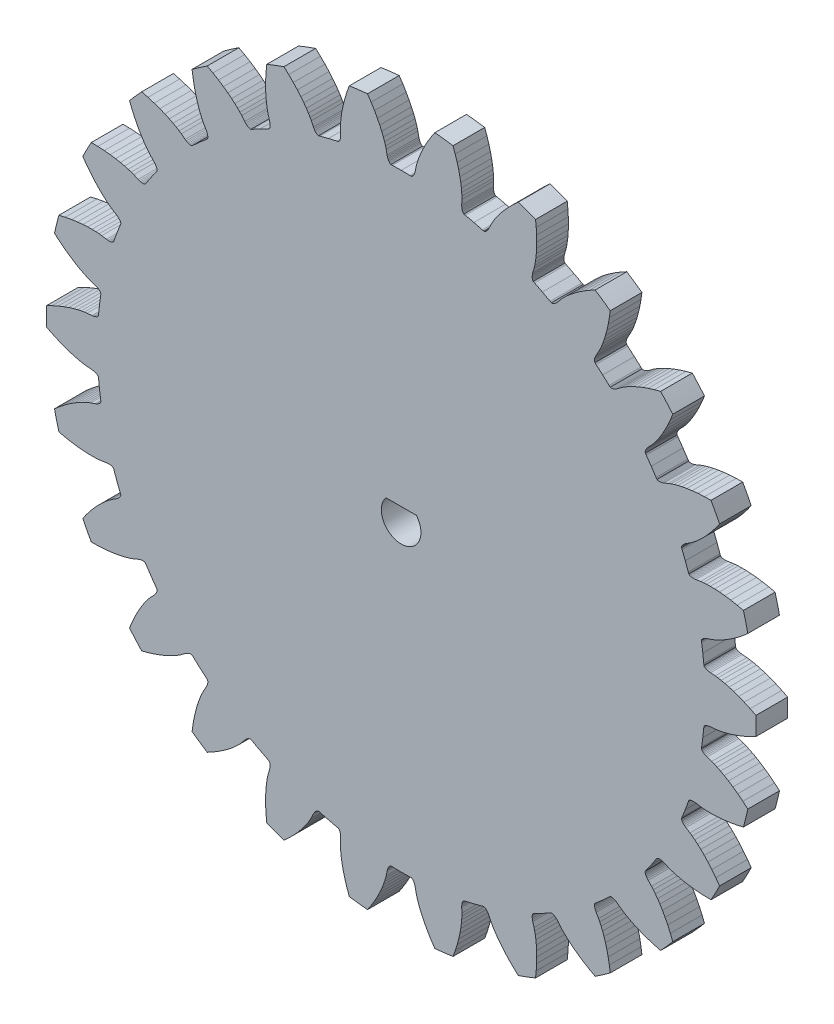
SolidWorks part; units mm, degrees
ref_plane "Front Plane" through (0, 0, 0) normal (0, 0, 1) x (1, 0, 0)
ref_plane "Top Plane" through (0, 0, 0) normal (0, 1, 0) x (1, 0, 0)
ref_plane "Right Plane" through (0, 0, 0) normal (1, 0, 0) x (0, 0, -1)
sketch "Model" plane through (0, 0, 0) normal (0, 0, 1) x (1, 0, 0)
  line L0 (53.9186, 11.3234) -> (53.1145, 10.6909)
  line L1 (53.1145, 10.6909) -> (52.3542, 10.1428)
  line L2 (52.3542, 10.1428) -> (51.6426, 9.6736)
  line L3 (51.6426, 9.6736) -> (50.9865, 9.2795)
  line L4 (50.9865, 9.2795) -> (50.3895, 8.954)
  line L5 (50.3895, 8.954) -> (49.8557, 8.6913)
  line L6 (49.8557, 8.6913) -> (49.3896, 8.4858)
  line L7 (49.3896, 8.4858) -> (48.9961, 8.3315)
  line L8 (48.9961, 8.3315) -> (48.275, 8.0914)
  line L9 (48.275, 8.0914) -> (48.0782, 8.0117)
  line L10 (48.0782, 8.0117) -> (47.9061, 7.9277)
  line L11 (47.9061, 7.9277) -> (47.7585, 7.8406)
  line L12 (47.7585, 7.8406) -> (47.6355, 7.7512)
  line L13 (47.6355, 7.7512) -> (47.5373, 7.6605)
  line L14 (47.5373, 7.6605) -> (47.4637, 7.5697)
  line L15 (47.4637, 7.5697) -> (47.4147, 7.4796)
  line L16 (47.4147, 7.4796) -> (47.3902, 7.3912)
  line L17 (47.3902, 7.3912) -> (47.3902, 7.3055)
  line L18 (47.3902, 7.3055) -> (47.4142, 7.1495)
  line L19 (47.4142, 7.1495) -> (47.6004, 5.7797)
  line L20 (47.6004, 5.7797) -> (47.7474, 4.4052)
  line L21 (47.7474, 4.4052) -> (47.7615, 4.248)
  line L22 (47.7615, 4.248) -> (47.782, 4.1648)
  line L23 (47.782, 4.1648) -> (47.8269, 4.0849)
  line L24 (47.8269, 4.0849) -> (47.896, 4.0091)
  line L25 (47.896, 4.0091) -> (47.9892, 3.9385)
  line L26 (47.9892, 3.9385) -> (48.1063, 3.874)
  line L27 (48.1063, 3.874) -> (48.2471, 3.8166)
  line L28 (48.2471, 3.8166) -> (48.4112, 3.7673)
  line L29 (48.4112, 3.7673) -> (48.5985, 3.727)
  line L30 (48.5985, 3.727) -> (48.8086, 3.6966)
  line L31 (48.8086, 3.6966) -> (49.5662, 3.6362)
  line L32 (49.5662, 3.6362) -> (49.9852, 3.5805)
  line L33 (49.9852, 3.5805) -> (50.4869, 3.4925)
  line L34 (50.4869, 3.4925) -> (51.0681, 3.3651)
  line L35 (51.0681, 3.3651) -> (51.7257, 3.192)
  line L36 (51.7257, 3.192) -> (52.457, 2.9663)
  line L37 (52.457, 2.9663) -> (53.2602, 2.6812)
  line L38 (53.2602, 2.6812) -> (54.1296, 2.3309)
  line L39 (54.1296, 2.3309) -> (55.0617, 1.9092)
  line L40 (55.0617, 1.9092) -> (55.9813, 1.447)
  line L41 (55.9813, -1.447) -> (55.0617, -1.9092)
  line L42 (55.0617, -1.9092) -> (54.1296, -2.3309)
  line L43 (54.1296, -2.3309) -> (53.2602, -2.6812)
  line L44 (53.2602, -2.6812) -> (52.457, -2.9663)
  line L45 (52.457, -2.9663) -> (51.7257, -3.192)
  line L46 (51.7257, -3.192) -> (51.0681, -3.3651)
  line L47 (51.0681, -3.3651) -> (50.4869, -3.4925)
  line L48 (50.4869, -3.4925) -> (49.9853, -3.5805)
  line L49 (49.9853, -3.5805) -> (49.5662, -3.6362)
  line L50 (49.5662, -3.6362) -> (48.8086, -3.6966)
  line L51 (48.8086, -3.6966) -> (48.5985, -3.727)
  line L52 (48.5985, -3.727) -> (48.4112, -3.7673)
  line L53 (48.4112, -3.7673) -> (48.2471, -3.8166)
  line L54 (48.2471, -3.8166) -> (48.1063, -3.874)
  line L55 (48.1063, -3.874) -> (47.9892, -3.9385)
  line L56 (47.9892, -3.9385) -> (47.896, -4.0091)
  line L57 (47.896, -4.0091) -> (47.8269, -4.0849)
  line L58 (47.8269, -4.0849) -> (47.782, -4.1648)
  line L59 (47.782, -4.1648) -> (47.7615, -4.248)
  line L60 (47.7615, -4.248) -> (47.7474, -4.4052)
  line L61 (47.7474, -4.4052) -> (47.6004, -5.7797)
  line L62 (47.6004, -5.7797) -> (47.4142, -7.1495)
  line L63 (47.4142, -7.1495) -> (47.3902, -7.3055)
  line L64 (47.3902, -7.3055) -> (47.3902, -7.3912)
  line L65 (47.3902, -7.3912) -> (47.4147, -7.4796)
  line L66 (47.4147, -7.4796) -> (47.4637, -7.5697)
  line L67 (47.4637, -7.5697) -> (47.5373, -7.6605)
  line L68 (47.5373, -7.6605) -> (47.6355, -7.7512)
  line L69 (47.6355, -7.7512) -> (47.7585, -7.8406)
  line L70 (47.7585, -7.8406) -> (47.9061, -7.9277)
  line L71 (47.9061, -7.9277) -> (48.0782, -8.0117)
  line L72 (48.0782, -8.0117) -> (48.275, -8.0914)
  line L73 (48.275, -8.0914) -> (48.9961, -8.3315)
  line L74 (48.9961, -8.3315) -> (49.3896, -8.4858)
  line L75 (49.3896, -8.4858) -> (49.8557, -8.6913)
  line L76 (49.8557, -8.6913) -> (50.3895, -8.954)
  line L77 (50.3895, -8.954) -> (50.9866, -9.2795)
  line L78 (50.9866, -9.2795) -> (51.6426, -9.6736)
  line L79 (51.6426, -9.6736) -> (52.3542, -10.1428)
  line L80 (52.3542, -10.1428) -> (53.1145, -10.6909)
  line L81 (53.1145, -10.6909) -> (53.9186, -11.3234)
  line L82 (53.9186, -11.3234) -> (54.7008, -11.9922)
  line L83 (54.0083, -14.8022) -> (53.0048, -15.0309)
  line L84 (53.0048, -15.0309) -> (51.9989, -15.2172)
  line L85 (51.9989, -15.2172) -> (51.071, -15.3493)
  line L86 (51.071, -15.3493) -> (50.2228, -15.4339)
  line L87 (50.2228, -15.4339) -> (49.4588, -15.478)
  line L88 (49.4588, -15.478) -> (48.7788, -15.4888)
  line L89 (48.7788, -15.4888) -> (48.1841, -15.4733)
  line L90 (48.1841, -15.4733) -> (47.6759, -15.4388)
  line L91 (47.6759, -15.4388) -> (47.2557, -15.3925)
  line L92 (47.2557, -15.3925) -> (46.5056, -15.2699)
  line L93 (46.5056, -15.2699) -> (46.2944, -15.2491)
  line L94 (46.2944, -15.2491) -> (46.1029, -15.2434)
  line L95 (46.1029, -15.2434) -> (45.9317, -15.252)
  line L96 (45.9317, -15.252) -> (45.7813, -15.274)
  line L97 (45.7813, -15.274) -> (45.6522, -15.3086)
  line L98 (45.6522, -15.3086) -> (45.5448, -15.3549)
  line L99 (45.5448, -15.3549) -> (45.4595, -15.4119)
  line L100 (45.4595, -15.4119) -> (45.3968, -15.4788)
  line L101 (45.3968, -15.4788) -> (45.357, -15.5546)
  line L102 (45.357, -15.5546) -> (45.3057, -15.7039)
  line L103 (45.3057, -15.7039) -> (44.834, -17.0033)
  line L104 (44.834, -17.0033) -> (44.3254, -18.2888)
  line L105 (44.3254, -18.2888) -> (44.2648, -18.4345)
  line L106 (44.2648, -18.4345) -> (44.2443, -18.5176)
  line L107 (44.2443, -18.5176) -> (44.2469, -18.6093)
  line L108 (44.2469, -18.6093) -> (44.2729, -18.7085)
  line L109 (44.2729, -18.7085) -> (44.3226, -18.8144)
  line L110 (44.3226, -18.8144) -> (44.3964, -18.9259)
  line L111 (44.3964, -18.9259) -> (44.4943, -19.0421)
  line L112 (44.4943, -19.0421) -> (44.6168, -19.1621)
  line L113 (44.6168, -19.1621) -> (44.7639, -19.2848)
  line L114 (44.7639, -19.2848) -> (44.9358, -19.4093)
  line L115 (44.9358, -19.4093) -> (45.5785, -19.8149)
  line L116 (45.5785, -19.8149) -> (45.9237, -20.0589)
  line L117 (45.9237, -20.0589) -> (46.327, -20.3701)
  line L118 (46.327, -20.3701) -> (46.7824, -20.7529)
  line L119 (46.7824, -20.7529) -> (47.2842, -21.2118)
  line L120 (47.2842, -21.2118) -> (47.8269, -21.7514)
  line L121 (47.8269, -21.7514) -> (48.4056, -22.3772)
  line L122 (48.4056, -22.3772) -> (49.0126, -23.0914)
  line L123 (49.0126, -23.0914) -> (49.6419, -23.898)
  line L124 (49.6419, -23.898) -> (50.2414, -24.7345)
  line L125 (48.8965, -27.2971) -> (47.8674, -27.279)
  line L126 (47.8674, -27.279) -> (46.8462, -27.2192)
  line L127 (46.8462, -27.2192) -> (45.9136, -27.1254)
  line L128 (45.9136, -27.1254) -> (45.0698, -27.0046)
  line L129 (45.0698, -27.0046) -> (44.3174, -26.8645)
  line L130 (44.3174, -26.8645) -> (43.6547, -26.7123)
  line L131 (43.6547, -26.7123) -> (43.0809, -26.5549)
  line L132 (43.0809, -26.5549) -> (42.5958, -26.3997)
  line L133 (42.5958, -26.3997) -> (42.1989, -26.2543)
  line L134 (42.1989, -26.2543) -> (41.4999, -25.9557)
  line L135 (41.4999, -25.9557) -> (41.2998, -25.885)
  line L136 (41.2998, -25.885) -> (41.1153, -25.8336)
  line L137 (41.1153, -25.8336) -> (40.947, -25.801)
  line L138 (40.947, -25.801) -> (40.7957, -25.7864)
  line L139 (40.7957, -25.7864) -> (40.662, -25.7891)
  line L140 (40.662, -25.7891) -> (40.5467, -25.8083)
  line L141 (40.5467, -25.8083) -> (40.4503, -25.8433)
  line L142 (40.4503, -25.8433) -> (40.3733, -25.8932)
  line L143 (40.3733, -25.8932) -> (40.3166, -25.9573)
  line L144 (40.3166, -25.9573) -> (40.231, -26.0899)
  line L145 (40.231, -26.0899) -> (39.4621, -27.2387)
  line L146 (39.4621, -27.2387) -> (38.6606, -28.3651)
  line L147 (38.6606, -28.3651) -> (38.5669, -28.4921)
  line L148 (38.5669, -28.4921) -> (38.5271, -28.5679)
  line L149 (38.5271, -28.5679) -> (38.5077, -28.6576)
  line L150 (38.5077, -28.6576) -> (38.5092, -28.7601)
  line L151 (38.5092, -28.7601) -> (38.5321, -28.8748)
  line L152 (38.5321, -28.8748) -> (38.577, -29.0007)
  line L153 (38.577, -29.0007) -> (38.6443, -29.137)
  line L154 (38.6443, -29.137) -> (38.7345, -29.2828)
  line L155 (38.7345, -29.2828) -> (38.8479, -29.4371)
  line L156 (38.8479, -29.4371) -> (38.9851, -29.5991)
  line L157 (38.9851, -29.5991) -> (39.5121, -30.1468)
  line L158 (39.5121, -30.1468) -> (39.7888, -30.4663)
  line L159 (39.7888, -30.4663) -> (40.1059, -30.8649)
  line L160 (40.1059, -30.8649) -> (40.4565, -31.3456)
  line L161 (40.4565, -31.3456) -> (40.8339, -31.9113)
  line L162 (40.8339, -31.9113) -> (41.2317, -32.5651)
  line L163 (41.2317, -32.5651) -> (41.6438, -33.3112)
  line L164 (41.6438, -33.3112) -> (42.0623, -34.1499)
  line L165 (42.0623, -34.1499) -> (42.4803, -35.0836)
  line L166 (42.4803, -35.0836) -> (42.8621, -36.0394)
  line L167 (40.943, -38.2056) -> (39.9482, -37.9417)
  line L168 (39.9482, -37.9417) -> (38.9709, -37.6393)
  line L169 (38.9709, -37.6393) -> (38.0879, -37.325)
  line L170 (38.0879, -37.325) -> (37.2976, -37.0058)
  line L171 (37.2976, -37.0058) -> (36.6006, -36.6898)
  line L172 (36.6006, -36.6898) -> (35.9935, -36.3833)
  line L173 (35.9935, -36.3833) -> (35.4741, -36.0932)
  line L174 (35.4741, -36.0932) -> (35.0402, -35.8264)
  line L175 (35.0402, -35.8264) -> (34.6896, -35.5902)
  line L176 (34.6896, -35.5902) -> (34.0824, -35.1331)
  line L177 (34.0824, -35.1331) -> (33.905, -35.0165)
  line L178 (33.905, -35.0165) -> (33.7381, -34.9225)
  line L179 (33.7381, -34.9225) -> (33.5826, -34.8505)
  line L180 (33.5826, -34.8505) -> (33.4392, -34.8001)
  line L181 (33.4392, -34.8001) -> (33.3087, -34.7708)
  line L182 (33.3087, -34.7708) -> (33.1922, -34.7618)
  line L183 (33.1922, -34.7618) -> (33.0902, -34.7727)
  line L184 (33.0902, -34.7727) -> (33.0035, -34.8028)
  line L185 (33.0035, -34.8028) -> (32.933, -34.8514)
  line L186 (32.933, -34.8514) -> (32.8183, -34.9597)
  line L187 (32.8183, -34.9597) -> (31.7967, -35.8911)
  line L188 (31.7967, -35.8911) -> (30.749, -36.7929)
  line L189 (30.749, -36.7929) -> (30.6276, -36.8938)
  line L190 (30.6276, -36.8938) -> (30.5708, -36.9579)
  line L191 (30.5708, -36.9579) -> (30.5305, -37.0403)
  line L192 (30.5305, -37.0403) -> (30.5074, -37.1403)
  line L193 (30.5074, -37.1403) -> (30.5023, -37.2571)
  line L194 (30.5023, -37.2571) -> (30.5157, -37.3901)
  line L195 (30.5157, -37.3901) -> (30.5485, -37.5385)
  line L196 (30.5485, -37.5385) -> (30.6011, -37.7016)
  line L197 (30.6011, -37.7016) -> (30.6743, -37.8786)
  line L198 (30.6743, -37.8786) -> (30.7687, -38.0688)
  line L199 (30.7687, -38.0688) -> (31.1493, -38.7267)
  line L200 (31.1493, -38.7267) -> (31.3416, -39.1031)
  line L201 (31.3416, -39.1031) -> (31.5541, -39.566)
  line L202 (31.5541, -39.566) -> (31.7794, -40.1166)
  line L203 (31.7794, -40.1166) -> (32.0105, -40.7562)
  line L204 (32.0105, -40.7562) -> (32.2402, -41.4862)
  line L205 (32.2402, -41.4862) -> (32.4618, -42.3093)
  line L206 (32.4618, -42.3093) -> (32.6674, -43.2238)
  line L207 (32.6674, -43.2238) -> (32.8498, -44.2304)
  line L208 (32.8498, -44.2304) -> (32.9918, -45.2497)
  line L209 (30.6101, -46.8937) -> (29.7073, -46.3995)
  line L210 (29.7073, -46.3995) -> (28.8308, -45.8719)
  line L211 (28.8308, -45.8719) -> (28.0487, -45.3554)
  line L212 (28.0487, -45.3554) -> (27.3577, -44.8564)
  line L213 (27.3577, -44.8564) -> (26.7566, -44.3827)
  line L214 (26.7566, -44.3827) -> (26.2405, -43.9399)
  line L215 (26.2405, -43.9399) -> (25.8056, -43.5339)
  line L216 (25.8056, -43.5339) -> (25.4481, -43.1711)
  line L217 (25.4481, -43.1711) -> (25.1643, -42.8578)
  line L218 (25.1643, -42.8578) -> (24.6841, -42.2687)
  line L219 (24.6841, -42.2687) -> (24.5398, -42.113)
  line L220 (24.5398, -42.113) -> (24.4003, -41.9818)
  line L221 (24.4003, -41.9818) -> (24.2664, -41.8747)
  line L222 (24.2664, -41.8747) -> (24.1392, -41.7914)
  line L223 (24.1392, -41.7914) -> (24.0197, -41.7317)
  line L224 (24.0197, -41.7317) -> (23.9086, -41.6951)
  line L225 (23.9086, -41.6951) -> (23.807, -41.6813)
  line L226 (23.807, -41.6813) -> (23.7157, -41.6897)
  line L227 (23.7157, -41.6897) -> (23.6356, -41.7201)
  line L228 (23.6356, -41.7201) -> (23.4982, -41.7978)
  line L229 (23.4982, -41.7978) -> (22.2835, -42.4577)
  line L230 (22.2835, -42.4577) -> (21.0503, -43.0825)
  line L231 (21.0503, -43.0825) -> (20.9084, -43.1515)
  line L232 (20.9084, -43.1515) -> (20.8379, -43.2001)
  line L233 (20.8379, -43.2001) -> (20.779, -43.2704)
  line L234 (20.779, -43.2704) -> (20.7327, -43.3619)
  line L235 (20.7327, -43.3619) -> (20.6997, -43.4741)
  line L236 (20.6997, -43.4741) -> (20.681, -43.6065)
  line L237 (20.681, -43.6065) -> (20.6772, -43.7585)
  line L238 (20.6772, -43.7585) -> (20.6893, -43.9294)
  line L239 (20.6893, -43.9294) -> (20.718, -44.1188)
  line L240 (20.718, -44.1188) -> (20.7642, -44.326)
  line L241 (20.7642, -44.326) -> (20.9763, -45.0559)
  line L242 (20.9763, -45.0559) -> (21.0728, -45.4674)
  line L243 (21.0728, -45.4674) -> (21.1684, -45.9677)
  line L244 (21.1684, -45.9677) -> (21.2554, -46.5563)
  line L245 (21.2554, -46.5563) -> (21.3267, -47.2325)
  line L246 (21.3267, -47.2325) -> (21.3751, -47.9963)
  line L247 (21.3751, -47.9963) -> (21.3932, -48.8485)
  line L248 (21.3932, -48.8485) -> (21.374, -49.7856)
  line L249 (21.374, -49.7856) -> (21.3102, -50.8066)
  line L250 (21.3102, -50.8066) -> (21.2042, -51.8303)
  line L251 (18.4982, -52.8566) -> (17.74, -52.1606)
  line L252 (17.74, -52.1606) -> (17.0152, -51.4387)
  line L253 (17.0152, -51.4387) -> (16.3794, -50.75)
  line L254 (16.3794, -50.75) -> (15.8279, -50.1001)
  line L255 (15.8279, -50.1001) -> (15.3576, -49.4963)
  line L256 (15.3576, -49.4963) -> (14.9625, -48.9429)
  line L257 (14.9625, -48.9429) -> (14.6374, -48.4446)
  line L258 (14.6374, -48.4446) -> (14.3771, -48.0067)
  line L259 (14.3771, -48.0067) -> (14.1765, -47.6347)
  line L260 (14.1765, -47.6347) -> (13.8513, -46.9477)
  line L261 (13.8513, -46.9477) -> (13.7484, -46.762)
  line L262 (13.7484, -46.762) -> (13.6444, -46.6012)
  line L263 (13.6444, -46.6012) -> (13.54, -46.4652)
  line L264 (13.54, -46.4652) -> (13.4365, -46.354)
  line L265 (13.4365, -46.354) -> (13.3346, -46.2673)
  line L266 (13.3346, -46.2673) -> (13.2356, -46.2052)
  line L267 (13.2356, -46.2052) -> (13.1402, -46.1675)
  line L268 (13.1402, -46.1675) -> (13.0495, -46.1538)
  line L269 (13.0495, -46.1538) -> (12.9645, -46.1642)
  line L270 (12.9645, -46.1642) -> (12.8125, -46.2067)
  line L271 (12.8125, -46.2067) -> (11.4752, -46.5567)
  line L272 (11.4752, -46.5567) -> (10.1283, -46.8683)
  line L273 (10.1283, -46.8683) -> (9.974, -46.9013)
  line L274 (9.974, -46.9013) -> (9.8939, -46.9316)
  line L275 (9.8939, -46.9316) -> (9.82, -46.9858)
  line L276 (9.82, -46.9858) -> (9.7531, -47.0636)
  line L277 (9.7531, -47.0636) -> (9.6942, -47.1646)
  line L278 (9.6942, -47.1646) -> (9.6443, -47.2886)
  line L279 (9.6443, -47.2886) -> (9.6043, -47.4353)
  line L280 (9.6043, -47.4353) -> (9.5751, -47.6042)
  line L281 (9.5751, -47.6042) -> (9.5577, -47.795)
  line L282 (9.5577, -47.795) -> (9.5529, -48.0072)
  line L283 (9.5529, -48.0072) -> (9.5842, -48.7666)
  line L284 (9.5842, -48.7666) -> (9.5795, -49.1893)
  line L285 (9.5795, -49.1893) -> (9.5525, -49.6979)
  line L286 (9.5525, -49.6979) -> (9.4962, -50.2902)
  line L287 (9.4962, -50.2902) -> (9.4035, -50.9639)
  line L288 (9.4035, -50.9639) -> (9.2677, -51.717)
  line L289 (9.2677, -51.717) -> (9.0814, -52.5488)
  line L290 (9.0814, -52.5488) -> (8.8385, -53.4541)
  line L291 (8.8385, -53.4541) -> (8.5322, -54.4301)
  line L292 (8.5322, -54.4301) -> (8.1842, -55.3987)
  line L293 (5.3113, -55.7476) -> (4.7417, -54.8904)
  line L294 (4.7417, -54.8904) -> (4.2107, -54.016)
  line L295 (4.2107, -54.016) -> (3.7582, -53.1951)
  line L296 (3.7582, -53.1951) -> (3.3782, -52.4321)
  line L297 (3.3782, -52.4321) -> (3.0661, -51.7334)
  line L298 (3.0661, -51.7334) -> (2.8149, -51.1014)
  line L299 (2.8149, -51.1014) -> (2.6185, -50.5398)
  line L300 (2.6185, -50.5398) -> (2.4706, -50.0524)
  line L301 (2.4706, -50.0524) -> (2.3649, -49.6432)
  line L302 (2.3649, -49.6432) -> (2.2135, -48.8983)
  line L303 (2.2135, -48.8983) -> (2.1581, -48.6934)
  line L304 (2.1581, -48.6934) -> (2.0955, -48.5124)
  line L305 (2.0955, -48.5124) -> (2.0267, -48.3554)
  line L306 (2.0267, -48.3554) -> (1.9528, -48.2226)
  line L307 (1.9528, -48.2226) -> (1.8747, -48.1141)
  line L308 (1.8747, -48.1141) -> (1.7933, -48.0301)
  line L309 (1.7933, -48.0301) -> (1.7098, -47.9706)
  line L310 (1.7098, -47.9706) -> (1.625, -47.9357)
  line L311 (1.625, -47.9357) -> (1.54, -47.9253)
  line L312 (1.54, -47.9253) -> (1.3822, -47.9303)
  line L313 (1.3822, -47.9303) -> (0, -47.95)
  line L314 (0, -47.95) -> (-1.3823, -47.9303)
  line L315 (-1.3823, -47.9303) -> (-1.54, -47.9253)
  line L316 (-1.54, -47.9253) -> (-1.6251, -47.9357)
  line L317 (-1.6251, -47.9357) -> (-1.7098, -47.9706)
  line L318 (-1.7098, -47.9706) -> (-1.7934, -48.0301)
  line L319 (-1.7934, -48.0301) -> (-1.8747, -48.1141)
  line L320 (-1.8747, -48.1141) -> (-1.9529, -48.2226)
  line L321 (-1.9529, -48.2226) -> (-2.0268, -48.3554)
  line L322 (-2.0268, -48.3554) -> (-2.0955, -48.5124)
  line L323 (-2.0955, -48.5124) -> (-2.1581, -48.6934)
  line L324 (-2.1581, -48.6934) -> (-2.2136, -48.8983)
  line L325 (-2.2136, -48.8983) -> (-2.3649, -49.6432)
  line L326 (-2.3649, -49.6432) -> (-2.4707, -50.0524)
  line L327 (-2.4707, -50.0524) -> (-2.6186, -50.5398)
  line L328 (-2.6186, -50.5398) -> (-2.815, -51.1014)
  line L329 (-2.815, -51.1014) -> (-3.0662, -51.7334)
  line L330 (-3.0662, -51.7334) -> (-3.3783, -52.4321)
  line L331 (-3.3783, -52.4321) -> (-3.7582, -53.1951)
  line L332 (-3.7582, -53.1951) -> (-4.2107, -54.016)
  line L333 (-4.2107, -54.016) -> (-4.7417, -54.8904)
  line L334 (-4.7417, -54.8904) -> (-5.3114, -55.7476)
  line L335 (-8.1843, -55.3987) -> (-8.5323, -54.4301)
  line L336 (-8.5323, -54.4301) -> (-8.8385, -53.454)
  line L337 (-8.8385, -53.454) -> (-9.0815, -52.5488)
  line L338 (-9.0815, -52.5488) -> (-9.2678, -51.717)
  line L339 (-9.2678, -51.717) -> (-9.4036, -50.9639)
  line L340 (-9.4036, -50.9639) -> (-9.4962, -50.2902)
  line L341 (-9.4962, -50.2902) -> (-9.5526, -49.6979)
  line L342 (-9.5526, -49.6979) -> (-9.5795, -49.1893)
  line L343 (-9.5795, -49.1893) -> (-9.5842, -48.7666)
  line L344 (-9.5842, -48.7666) -> (-9.553, -48.0072)
  line L345 (-9.553, -48.0072) -> (-9.5578, -47.795)
  line L346 (-9.5578, -47.795) -> (-9.5752, -47.6042)
  line L347 (-9.5752, -47.6042) -> (-9.6044, -47.4353)
  line L348 (-9.6044, -47.4353) -> (-9.6444, -47.2886)
  line L349 (-9.6444, -47.2886) -> (-9.6943, -47.1646)
  line L350 (-9.6943, -47.1646) -> (-9.7531, -47.0636)
  line L351 (-9.7531, -47.0636) -> (-9.82, -46.9858)
  line L352 (-9.82, -46.9858) -> (-9.894, -46.9316)
  line L353 (-9.894, -46.9316) -> (-9.9741, -46.9013)
  line L354 (-9.9741, -46.9013) -> (-10.1284, -46.8683)
  line L355 (-10.1284, -46.8683) -> (-11.4752, -46.5567)
  line L356 (-11.4752, -46.5567) -> (-12.8126, -46.2067)
  line L357 (-12.8126, -46.2067) -> (-12.9646, -46.1642)
  line L358 (-12.9646, -46.1642) -> (-13.0496, -46.1538)
  line L359 (-13.0496, -46.1538) -> (-13.1403, -46.1675)
  line L360 (-13.1403, -46.1675) -> (-13.2356, -46.2052)
  line L361 (-13.2356, -46.2052) -> (-13.3347, -46.2673)
  line L362 (-13.3347, -46.2673) -> (-13.4365, -46.354)
  line L363 (-13.4365, -46.354) -> (-13.5401, -46.4652)
  line L364 (-13.5401, -46.4652) -> (-13.6444, -46.6012)
  line L365 (-13.6444, -46.6012) -> (-13.7485, -46.762)
  line L366 (-13.7485, -46.762) -> (-13.8514, -46.9477)
  line L367 (-13.8514, -46.9477) -> (-14.1766, -47.6347)
  line L368 (-14.1766, -47.6347) -> (-14.3772, -48.0067)
  line L369 (-14.3772, -48.0067) -> (-14.6375, -48.4446)
  line L370 (-14.6375, -48.4446) -> (-14.9626, -48.9429)
  line L371 (-14.9626, -48.9429) -> (-15.3577, -49.4963)
  line L372 (-15.3577, -49.4963) -> (-15.828, -50.1)
  line L373 (-15.828, -50.1) -> (-16.3795, -50.75)
  line L374 (-16.3795, -50.75) -> (-17.0153, -51.4387)
  line L375 (-17.0153, -51.4387) -> (-17.7401, -52.1606)
  line L376 (-17.7401, -52.1606) -> (-18.4983, -52.8565)
  line L377 (-21.2043, -51.8303) -> (-21.3103, -50.8066)
  line L378 (-21.3103, -50.8066) -> (-21.3741, -49.7856)
  line L379 (-21.3741, -49.7856) -> (-21.3933, -48.8485)
  line L380 (-21.3933, -48.8485) -> (-21.3751, -47.9963)
  line L381 (-21.3751, -47.9963) -> (-21.3268, -47.2325)
  line L382 (-21.3268, -47.2325) -> (-21.2555, -46.5563)
  line L383 (-21.2555, -46.5563) -> (-21.1685, -45.9677)
  line L384 (-21.1685, -45.9677) -> (-21.0729, -45.4674)
  line L385 (-21.0729, -45.4674) -> (-20.9763, -45.0559)
  line L386 (-20.9763, -45.0559) -> (-20.7642, -44.326)
  line L387 (-20.7642, -44.326) -> (-20.7181, -44.1188)
  line L388 (-20.7181, -44.1188) -> (-20.6894, -43.9294)
  line L389 (-20.6894, -43.9294) -> (-20.6773, -43.7584)
  line L390 (-20.6773, -43.7584) -> (-20.681, -43.6065)
  line L391 (-20.681, -43.6065) -> (-20.6998, -43.4741)
  line L392 (-20.6998, -43.4741) -> (-20.7328, -43.3619)
  line L393 (-20.7328, -43.3619) -> (-20.7791, -43.2704)
  line L394 (-20.7791, -43.2704) -> (-20.8379, -43.2001)
  line L395 (-20.8379, -43.2001) -> (-20.9084, -43.1514)
  line L396 (-20.9084, -43.1514) -> (-21.0504, -43.0825)
  line L397 (-21.0504, -43.0825) -> (-22.2835, -42.4577)
  line L398 (-22.2835, -42.4577) -> (-23.4983, -41.7978)
  line L399 (-23.4983, -41.7978) -> (-23.6356, -41.7201)
  line L400 (-23.6356, -41.7201) -> (-23.7157, -41.6897)
  line L401 (-23.7157, -41.6897) -> (-23.807, -41.6813)
  line L402 (-23.807, -41.6813) -> (-23.9087, -41.6951)
  line L403 (-23.9087, -41.6951) -> (-24.0197, -41.7317)
  line L404 (-24.0197, -41.7317) -> (-24.1393, -41.7914)
  line L405 (-24.1393, -41.7914) -> (-24.2665, -41.8747)
  line L406 (-24.2665, -41.8747) -> (-24.4003, -41.9818)
  line L407 (-24.4003, -41.9818) -> (-24.5399, -42.113)
  line L408 (-24.5399, -42.113) -> (-24.6842, -42.2686)
  line L409 (-24.6842, -42.2686) -> (-25.1644, -42.8578)
  line L410 (-25.1644, -42.8578) -> (-25.4482, -43.1711)
  line L411 (-25.4482, -43.1711) -> (-25.8057, -43.5339)
  line L412 (-25.8057, -43.5339) -> (-26.2406, -43.9399)
  line L413 (-26.2406, -43.9399) -> (-26.7566, -44.3827)
  line L414 (-26.7566, -44.3827) -> (-27.3577, -44.8564)
  line L415 (-27.3577, -44.8564) -> (-28.0488, -45.3554)
  line L416 (-28.0488, -45.3554) -> (-28.8309, -45.8719)
  line L417 (-28.8309, -45.8719) -> (-29.7074, -46.3995)
  line L418 (-29.7074, -46.3995) -> (-30.6101, -46.8937)
  line L419 (-32.9919, -45.2497) -> (-32.8499, -44.2304)
  line L420 (-32.8499, -44.2304) -> (-32.6675, -43.2238)
  line L421 (-32.6675, -43.2238) -> (-32.4619, -42.3093)
  line L422 (-32.4619, -42.3093) -> (-32.2403, -41.4862)
  line L423 (-32.2403, -41.4862) -> (-32.0106, -40.7562)
  line L424 (-32.0106, -40.7562) -> (-31.7795, -40.1166)
  line L425 (-31.7795, -40.1166) -> (-31.5541, -39.566)
  line L426 (-31.5541, -39.566) -> (-31.3416, -39.1031)
  line L427 (-31.3416, -39.1031) -> (-31.1494, -38.7267)
  line L428 (-31.1494, -38.7267) -> (-30.7688, -38.0688)
  line L429 (-30.7688, -38.0688) -> (-30.6744, -37.8786)
  line L430 (-30.6744, -37.8786) -> (-30.6012, -37.7016)
  line L431 (-30.6012, -37.7016) -> (-30.5485, -37.5385)
  line L432 (-30.5485, -37.5385) -> (-30.5158, -37.3901)
  line L433 (-30.5158, -37.3901) -> (-30.5023, -37.2571)
  line L434 (-30.5023, -37.2571) -> (-30.5075, -37.1402)
  line L435 (-30.5075, -37.1402) -> (-30.5306, -37.0403)
  line L436 (-30.5306, -37.0403) -> (-30.5709, -36.9579)
  line L437 (-30.5709, -36.9579) -> (-30.6277, -36.8938)
  line L438 (-30.6277, -36.8938) -> (-30.749, -36.7929)
  line L439 (-30.749, -36.7929) -> (-31.7968, -35.8911)
  line L440 (-31.7968, -35.8911) -> (-32.8183, -34.9597)
  line L441 (-32.8183, -34.9597) -> (-32.9331, -34.8514)
  line L442 (-32.9331, -34.8514) -> (-33.0036, -34.8028)
  line L443 (-33.0036, -34.8028) -> (-33.0902, -34.7727)
  line L444 (-33.0902, -34.7727) -> (-33.1922, -34.7618)
  line L445 (-33.1922, -34.7618) -> (-33.3088, -34.7708)
  line L446 (-33.3088, -34.7708) -> (-33.4392, -34.8001)
  line L447 (-33.4392, -34.8001) -> (-33.5826, -34.8505)
  line L448 (-33.5826, -34.8505) -> (-33.7382, -34.9225)
  line L449 (-33.7382, -34.9225) -> (-33.9051, -35.0165)
  line L450 (-33.9051, -35.0165) -> (-34.0825, -35.1331)
  line L451 (-34.0825, -35.1331) -> (-34.6897, -35.5902)
  line L452 (-34.6897, -35.5902) -> (-35.0402, -35.8264)
  line L453 (-35.0402, -35.8264) -> (-35.4741, -36.0932)
  line L454 (-35.4741, -36.0932) -> (-35.9936, -36.3833)
  line L455 (-35.9936, -36.3833) -> (-36.6006, -36.6898)
  line L456 (-36.6006, -36.6898) -> (-37.2976, -37.0058)
  line L457 (-37.2976, -37.0058) -> (-38.088, -37.325)
  line L458 (-38.088, -37.325) -> (-38.971, -37.6393)
  line L459 (-38.971, -37.6393) -> (-39.9483, -37.9417)
  line L460 (-39.9483, -37.9417) -> (-40.9431, -38.2056)
  line L461 (-42.8622, -36.0394) -> (-42.4803, -35.0836)
  line L462 (-42.4803, -35.0836) -> (-42.0623, -34.1499)
  line L463 (-42.0623, -34.1499) -> (-41.6439, -33.3112)
  line L464 (-41.6439, -33.3112) -> (-41.2317, -32.5651)
  line L465 (-41.2317, -32.5651) -> (-40.834, -31.9113)
  line L466 (-40.834, -31.9113) -> (-40.4566, -31.3456)
  line L467 (-40.4566, -31.3456) -> (-40.106, -30.8649)
  line L468 (-40.106, -30.8649) -> (-39.7889, -30.4663)
  line L469 (-39.7889, -30.4663) -> (-39.5121, -30.1468)
  line L470 (-39.5121, -30.1468) -> (-38.9851, -29.5991)
  line L471 (-38.9851, -29.5991) -> (-38.848, -29.4371)
  line L472 (-38.848, -29.4371) -> (-38.7346, -29.2827)
  line L473 (-38.7346, -29.2827) -> (-38.6444, -29.137)
  line L474 (-38.6444, -29.137) -> (-38.5771, -29.0007)
  line L475 (-38.5771, -29.0007) -> (-38.5322, -28.8748)
  line L476 (-38.5322, -28.8748) -> (-38.5092, -28.7601)
  line L477 (-38.5092, -28.7601) -> (-38.5078, -28.6575)
  line L478 (-38.5078, -28.6575) -> (-38.5272, -28.5679)
  line L479 (-38.5272, -28.5679) -> (-38.567, -28.4921)
  line L480 (-38.567, -28.4921) -> (-38.6607, -28.3651)
  line L481 (-38.6607, -28.3651) -> (-39.4621, -27.2387)
  line L482 (-39.4621, -27.2387) -> (-40.2311, -26.0899)
  line L483 (-40.2311, -26.0899) -> (-40.3166, -25.9573)
  line L484 (-40.3166, -25.9573) -> (-40.3734, -25.8932)
  line L485 (-40.3734, -25.8932) -> (-40.4503, -25.8433)
  line L486 (-40.4503, -25.8433) -> (-40.5467, -25.8083)
  line L487 (-40.5467, -25.8083) -> (-40.6621, -25.7891)
  line L488 (-40.6621, -25.7891) -> (-40.7957, -25.7864)
  line L489 (-40.7957, -25.7864) -> (-40.947, -25.801)
  line L490 (-40.947, -25.801) -> (-41.1153, -25.8336)
  line L491 (-41.1153, -25.8336) -> (-41.2999, -25.885)
  line L492 (-41.2999, -25.885) -> (-41.5, -25.9557)
  line L493 (-41.5, -25.9557) -> (-42.199, -26.2543)
  line L494 (-42.199, -26.2543) -> (-42.5958, -26.3997)
  line L495 (-42.5958, -26.3997) -> (-43.081, -26.5549)
  line L496 (-43.081, -26.5549) -> (-43.6548, -26.7123)
  line L497 (-43.6548, -26.7123) -> (-44.3175, -26.8645)
  line L498 (-44.3175, -26.8645) -> (-45.0699, -27.0046)
  line L499 (-45.0699, -27.0046) -> (-45.9137, -27.1253)
  line L500 (-45.9137, -27.1253) -> (-46.8462, -27.2192)
  line L501 (-46.8462, -27.2192) -> (-47.8675, -27.279)
  line L502 (-47.8675, -27.279) -> (-48.8965, -27.2971)
  line L503 (-50.2415, -24.7345) -> (-49.642, -23.898)
  line L504 (-49.642, -23.898) -> (-49.0127, -23.0914)
  line L505 (-49.0127, -23.0914) -> (-48.4057, -22.3772)
  line L506 (-48.4057, -22.3772) -> (-47.8269, -21.7514)
  line L507 (-47.8269, -21.7514) -> (-47.2843, -21.2118)
  line L508 (-47.2843, -21.2118) -> (-46.7825, -20.7529)
  line L509 (-46.7825, -20.7529) -> (-46.327, -20.3701)
  line L510 (-46.327, -20.3701) -> (-45.9237, -20.0589)
  line L511 (-45.9237, -20.0589) -> (-45.5786, -19.8149)
  line L512 (-45.5786, -19.8149) -> (-44.9358, -19.4093)
  line L513 (-44.9358, -19.4093) -> (-44.7639, -19.2848)
  line L514 (-44.7639, -19.2848) -> (-44.6168, -19.1621)
  line L515 (-44.6168, -19.1621) -> (-44.4944, -19.0421)
  line L516 (-44.4944, -19.0421) -> (-44.3964, -18.9259)
  line L517 (-44.3964, -18.9259) -> (-44.3227, -18.8144)
  line L518 (-44.3227, -18.8144) -> (-44.273, -18.7085)
  line L519 (-44.273, -18.7085) -> (-44.247, -18.6093)
  line L520 (-44.247, -18.6093) -> (-44.2444, -18.5177)
  line L521 (-44.2444, -18.5177) -> (-44.2649, -18.4345)
  line L522 (-44.2649, -18.4345) -> (-44.3255, -18.2888)
  line L523 (-44.3255, -18.2888) -> (-44.8341, -17.0033)
  line L524 (-44.8341, -17.0033) -> (-45.3058, -15.7039)
  line L525 (-45.3058, -15.7039) -> (-45.3571, -15.5546)
  line L526 (-45.3571, -15.5546) -> (-45.3969, -15.4788)
  line L527 (-45.3969, -15.4788) -> (-45.4596, -15.4119)
  line L528 (-45.4596, -15.4119) -> (-45.5449, -15.3549)
  line L529 (-45.5449, -15.3549) -> (-45.6523, -15.3086)
  line L530 (-45.6523, -15.3086) -> (-45.7814, -15.274)
  line L531 (-45.7814, -15.274) -> (-45.9318, -15.252)
  line L532 (-45.9318, -15.252) -> (-46.103, -15.2434)
  line L533 (-46.103, -15.2434) -> (-46.2944, -15.2491)
  line L534 (-46.2944, -15.2491) -> (-46.5057, -15.2699)
  line L535 (-46.5057, -15.2699) -> (-47.2558, -15.3925)
  line L536 (-47.2558, -15.3925) -> (-47.6759, -15.4388)
  line L537 (-47.6759, -15.4388) -> (-48.1841, -15.4733)
  line L538 (-48.1841, -15.4733) -> (-48.7789, -15.4888)
  line L539 (-48.7789, -15.4888) -> (-49.4588, -15.478)
  line L540 (-49.4588, -15.478) -> (-50.2228, -15.434)
  line L541 (-50.2228, -15.434) -> (-51.071, -15.3493)
  line L542 (-51.071, -15.3493) -> (-51.999, -15.2172)
  line L543 (-51.999, -15.2172) -> (-53.0048, -15.0309)
  line L544 (-53.0048, -15.0309) -> (-54.0083, -14.8022)
  line L545 (-54.7009, -11.9922) -> (-53.9187, -11.3234)
  line L546 (-53.9187, -11.3234) -> (-53.1146, -10.6909)
  line L547 (-53.1146, -10.6909) -> (-52.3543, -10.1428)
  line L548 (-52.3543, -10.1428) -> (-51.6426, -9.6736)
  line L549 (-51.6426, -9.6736) -> (-50.9866, -9.2795)
  line L550 (-50.9866, -9.2795) -> (-50.3896, -8.954)
  line L551 (-50.3896, -8.954) -> (-49.8557, -8.6914)
  line L552 (-49.8557, -8.6914) -> (-49.3897, -8.4858)
  line L553 (-49.3897, -8.4858) -> (-48.9962, -8.3315)
  line L554 (-48.9962, -8.3315) -> (-48.275, -8.0914)
  line L555 (-48.275, -8.0914) -> (-48.0783, -8.0117)
  line L556 (-48.0783, -8.0117) -> (-47.9061, -7.9278)
  line L557 (-47.9061, -7.9278) -> (-47.7585, -7.8406)
  line L558 (-47.7585, -7.8406) -> (-47.6356, -7.7512)
  line L559 (-47.6356, -7.7512) -> (-47.5373, -7.6606)
  line L560 (-47.5373, -7.6606) -> (-47.4637, -7.5697)
  line L561 (-47.4637, -7.5697) -> (-47.4147, -7.4796)
  line L562 (-47.4147, -7.4796) -> (-47.3903, -7.3912)
  line L563 (-47.3903, -7.3912) -> (-47.3903, -7.3055)
  line L564 (-47.3903, -7.3055) -> (-47.4142, -7.1495)
  line L565 (-47.4142, -7.1495) -> (-47.6005, -5.7797)
  line L566 (-47.6005, -5.7797) -> (-47.7474, -4.4052)
  line L567 (-47.7474, -4.4052) -> (-47.7615, -4.248)
  line L568 (-47.7615, -4.248) -> (-47.782, -4.1648)
  line L569 (-47.782, -4.1648) -> (-47.8269, -4.0849)
  line L570 (-47.8269, -4.0849) -> (-47.8961, -4.0091)
  line L571 (-47.8961, -4.0091) -> (-47.9893, -3.9385)
  line L572 (-47.9893, -3.9385) -> (-48.1064, -3.874)
  line L573 (-48.1064, -3.874) -> (-48.2471, -3.8166)
  line L574 (-48.2471, -3.8166) -> (-48.4113, -3.7673)
  line L575 (-48.4113, -3.7673) -> (-48.5986, -3.727)
  line L576 (-48.5986, -3.727) -> (-48.8086, -3.6967)
  line L577 (-48.8086, -3.6967) -> (-49.5663, -3.6362)
  line L578 (-49.5663, -3.6362) -> (-49.9853, -3.5805)
  line L579 (-49.9853, -3.5805) -> (-50.487, -3.4925)
  line L580 (-50.487, -3.4925) -> (-51.0682, -3.3652)
  line L581 (-51.0682, -3.3652) -> (-51.7258, -3.192)
  line L582 (-51.7258, -3.192) -> (-52.457, -2.9664)
  line L583 (-52.457, -2.9664) -> (-53.2603, -2.6812)
  line L584 (-53.2603, -2.6812) -> (-54.1297, -2.3309)
  line L585 (-54.1297, -2.3309) -> (-55.0617, -1.9092)
  line L586 (-55.0617, -1.9092) -> (-55.9813, -1.447)
  line L587 (-55.9813, 1.447) -> (-55.0617, 1.9092)
  line L588 (-55.0617, 1.9092) -> (-54.1297, 2.3309)
  line L589 (-54.1297, 2.3309) -> (-53.2603, 2.6811)
  line L590 (-53.2603, 2.6811) -> (-52.457, 2.9663)
  line L591 (-52.457, 2.9663) -> (-51.7258, 3.192)
  line L592 (-51.7258, 3.192) -> (-51.0682, 3.3651)
  line L593 (-51.0682, 3.3651) -> (-50.487, 3.4924)
  line L594 (-50.487, 3.4924) -> (-49.9853, 3.5805)
  line L595 (-49.9853, 3.5805) -> (-49.5663, 3.6362)
  line L596 (-49.5663, 3.6362) -> (-48.8086, 3.6966)
  line L597 (-48.8086, 3.6966) -> (-48.5986, 3.727)
  line L598 (-48.5986, 3.727) -> (-48.4113, 3.7673)
  line L599 (-48.4113, 3.7673) -> (-48.2471, 3.8166)
  line L600 (-48.2471, 3.8166) -> (-48.1064, 3.874)
  line L601 (-48.1064, 3.874) -> (-47.9893, 3.9385)
  line L602 (-47.9893, 3.9385) -> (-47.8961, 4.0091)
  line L603 (-47.8961, 4.0091) -> (-47.8269, 4.0849)
  line L604 (-47.8269, 4.0849) -> (-47.782, 4.1648)
  line L605 (-47.782, 4.1648) -> (-47.7615, 4.248)
  line L606 (-47.7615, 4.248) -> (-47.7474, 4.4052)
  line L607 (-47.7474, 4.4052) -> (-47.6005, 5.7797)
  line L608 (-47.6005, 5.7797) -> (-47.4142, 7.1495)
  line L609 (-47.4142, 7.1495) -> (-47.3903, 7.3055)
  line L610 (-47.3903, 7.3055) -> (-47.3903, 7.3912)
  line L611 (-47.3903, 7.3912) -> (-47.4147, 7.4795)
  line L612 (-47.4147, 7.4795) -> (-47.4637, 7.5697)
  line L613 (-47.4637, 7.5697) -> (-47.5373, 7.6605)
  line L614 (-47.5373, 7.6605) -> (-47.6356, 7.7512)
  line L615 (-47.6356, 7.7512) -> (-47.7585, 7.8406)
  line L616 (-47.7585, 7.8406) -> (-47.9061, 7.9277)
  line L617 (-47.9061, 7.9277) -> (-48.0783, 8.0117)
  line L618 (-48.0783, 8.0117) -> (-48.275, 8.0914)
  line L619 (-48.275, 8.0914) -> (-48.9962, 8.3315)
  line L620 (-48.9962, 8.3315) -> (-49.3897, 8.4858)
  line L621 (-49.3897, 8.4858) -> (-49.8557, 8.6913)
  line L622 (-49.8557, 8.6913) -> (-50.3896, 8.954)
  line L623 (-50.3896, 8.954) -> (-50.9866, 9.2795)
  line L624 (-50.9866, 9.2795) -> (-51.6426, 9.6736)
  line L625 (-51.6426, 9.6736) -> (-52.3543, 10.1427)
  line L626 (-52.3543, 10.1427) -> (-53.1146, 10.6909)
  line L627 (-53.1146, 10.6909) -> (-53.9187, 11.3234)
  line L628 (-53.9187, 11.3234) -> (-54.7009, 11.9922)
  line L629 (-54.0083, 14.8021) -> (-53.0049, 15.0308)
  line L630 (-53.0049, 15.0308) -> (-51.999, 15.2172)
  line L631 (-51.999, 15.2172) -> (-51.071, 15.3492)
  line L632 (-51.071, 15.3492) -> (-50.2228, 15.4339)
  line L633 (-50.2228, 15.4339) -> (-49.4588, 15.478)
  line L634 (-49.4588, 15.478) -> (-48.7789, 15.4887)
  line L635 (-48.7789, 15.4887) -> (-48.1841, 15.4733)
  line L636 (-48.1841, 15.4733) -> (-47.6759, 15.4387)
  line L637 (-47.6759, 15.4387) -> (-47.2558, 15.3925)
  line L638 (-47.2558, 15.3925) -> (-46.5057, 15.2699)
  line L639 (-46.5057, 15.2699) -> (-46.2944, 15.2491)
  line L640 (-46.2944, 15.2491) -> (-46.103, 15.2434)
  line L641 (-46.103, 15.2434) -> (-45.9318, 15.252)
  line L642 (-45.9318, 15.252) -> (-45.7814, 15.274)
  line L643 (-45.7814, 15.274) -> (-45.6523, 15.3086)
  line L644 (-45.6523, 15.3086) -> (-45.5449, 15.3548)
  line L645 (-45.5449, 15.3548) -> (-45.4596, 15.4119)
  line L646 (-45.4596, 15.4119) -> (-45.3969, 15.4788)
  line L647 (-45.3969, 15.4788) -> (-45.3571, 15.5546)
  line L648 (-45.3571, 15.5546) -> (-45.3058, 15.7038)
  line L649 (-45.3058, 15.7038) -> (-44.8341, 17.0033)
  line L650 (-44.8341, 17.0033) -> (-44.3255, 18.2887)
  line L651 (-44.3255, 18.2887) -> (-44.2649, 18.4345)
  line L652 (-44.2649, 18.4345) -> (-44.2444, 18.5176)
  line L653 (-44.2444, 18.5176) -> (-44.247, 18.6093)
  line L654 (-44.247, 18.6093) -> (-44.273, 18.7085)
  line L655 (-44.273, 18.7085) -> (-44.3227, 18.8143)
  line L656 (-44.3227, 18.8143) -> (-44.3964, 18.9259)
  line L657 (-44.3964, 18.9259) -> (-44.4944, 19.0421)
  line L658 (-44.4944, 19.0421) -> (-44.6168, 19.162)
  line L659 (-44.6168, 19.162) -> (-44.7639, 19.2847)
  line L660 (-44.7639, 19.2847) -> (-44.9358, 19.4092)
  line L661 (-44.9358, 19.4092) -> (-45.5786, 19.8149)
  line L662 (-45.5786, 19.8149) -> (-45.9238, 20.0589)
  line L663 (-45.9238, 20.0589) -> (-46.327, 20.37)
  line L664 (-46.327, 20.37) -> (-46.7825, 20.7528)
  line L665 (-46.7825, 20.7528) -> (-47.2843, 21.2118)
  line L666 (-47.2843, 21.2118) -> (-47.8269, 21.7514)
  line L667 (-47.8269, 21.7514) -> (-48.4057, 22.3772)
  line L668 (-48.4057, 22.3772) -> (-49.0127, 23.0914)
  line L669 (-49.0127, 23.0914) -> (-49.642, 23.8979)
  line L670 (-49.642, 23.8979) -> (-50.2415, 24.7345)
  line L671 (-48.8965, 27.2971) -> (-47.8675, 27.279)
  line L672 (-47.8675, 27.279) -> (-46.8462, 27.2192)
  line L673 (-46.8462, 27.2192) -> (-45.9137, 27.1253)
  line L674 (-45.9137, 27.1253) -> (-45.0699, 27.0046)
  line L675 (-45.0699, 27.0046) -> (-44.3175, 26.8645)
  line L676 (-44.3175, 26.8645) -> (-43.6548, 26.7122)
  line L677 (-43.6548, 26.7122) -> (-43.081, 26.5549)
  line L678 (-43.081, 26.5549) -> (-42.5958, 26.3997)
  line L679 (-42.5958, 26.3997) -> (-42.199, 26.2543)
  line L680 (-42.199, 26.2543) -> (-41.5, 25.9557)
  line L681 (-41.5, 25.9557) -> (-41.2999, 25.8849)
  line L682 (-41.2999, 25.8849) -> (-41.1153, 25.8336)
  line L683 (-41.1153, 25.8336) -> (-40.947, 25.801)
  line L684 (-40.947, 25.801) -> (-40.7957, 25.7864)
  line L685 (-40.7957, 25.7864) -> (-40.6621, 25.7891)
  line L686 (-40.6621, 25.7891) -> (-40.5467, 25.8083)
  line L687 (-40.5467, 25.8083) -> (-40.4503, 25.8432)
  line L688 (-40.4503, 25.8432) -> (-40.3734, 25.8932)
  line L689 (-40.3734, 25.8932) -> (-40.3166, 25.9573)
  line L690 (-40.3166, 25.9573) -> (-40.2311, 26.0899)
  line L691 (-40.2311, 26.0899) -> (-39.4621, 27.2387)
  line L692 (-39.4621, 27.2387) -> (-38.6607, 28.3651)
  line L693 (-38.6607, 28.3651) -> (-38.567, 28.4921)
  line L694 (-38.567, 28.4921) -> (-38.5272, 28.5679)
  line L695 (-38.5272, 28.5679) -> (-38.5077, 28.6575)
  line L696 (-38.5077, 28.6575) -> (-38.5092, 28.7601)
  line L697 (-38.5092, 28.7601) -> (-38.5322, 28.8748)
  line L698 (-38.5322, 28.8748) -> (-38.5771, 29.0007)
  line L699 (-38.5771, 29.0007) -> (-38.6444, 29.137)
  line L700 (-38.6444, 29.137) -> (-38.7346, 29.2827)
  line L701 (-38.7346, 29.2827) -> (-38.848, 29.4371)
  line L702 (-38.848, 29.4371) -> (-38.9851, 29.5991)
  line L703 (-38.9851, 29.5991) -> (-39.5121, 30.1468)
  line L704 (-39.5121, 30.1468) -> (-39.7889, 30.4663)
  line L705 (-39.7889, 30.4663) -> (-40.106, 30.8649)
  line L706 (-40.106, 30.8649) -> (-40.4566, 31.3456)
  line L707 (-40.4566, 31.3456) -> (-40.834, 31.9113)
  line L708 (-40.834, 31.9113) -> (-41.2317, 32.5651)
  line L709 (-41.2317, 32.5651) -> (-41.6439, 33.3112)
  line L710 (-41.6439, 33.3112) -> (-42.0623, 34.1499)
  line L711 (-42.0623, 34.1499) -> (-42.4803, 35.0836)
  line L712 (-42.4803, 35.0836) -> (-42.8622, 36.0393)
  line L713 (-40.9431, 38.2056) -> (-39.9483, 37.9417)
  line L714 (-39.9483, 37.9417) -> (-38.971, 37.6393)
  line L715 (-38.971, 37.6393) -> (-38.088, 37.325)
  line L716 (-38.088, 37.325) -> (-37.2976, 37.0058)
  line L717 (-37.2976, 37.0058) -> (-36.6006, 36.6897)
  line L718 (-36.6006, 36.6897) -> (-35.9936, 36.3833)
  line L719 (-35.9936, 36.3833) -> (-35.4741, 36.0932)
  line L720 (-35.4741, 36.0932) -> (-35.0402, 35.8264)
  line L721 (-35.0402, 35.8264) -> (-34.6897, 35.5902)
  line L722 (-34.6897, 35.5902) -> (-34.0825, 35.1331)
  line L723 (-34.0825, 35.1331) -> (-33.9051, 35.0165)
  line L724 (-33.9051, 35.0165) -> (-33.7382, 34.9224)
  line L725 (-33.7382, 34.9224) -> (-33.5826, 34.8505)
  line L726 (-33.5826, 34.8505) -> (-33.4392, 34.8001)
  line L727 (-33.4392, 34.8001) -> (-33.3088, 34.7707)
  line L728 (-33.3088, 34.7707) -> (-33.1922, 34.7618)
  line L729 (-33.1922, 34.7618) -> (-33.0902, 34.7727)
  line L730 (-33.0902, 34.7727) -> (-33.0036, 34.8027)
  line L731 (-33.0036, 34.8027) -> (-32.9331, 34.8514)
  line L732 (-32.9331, 34.8514) -> (-32.8183, 34.9597)
  line L733 (-32.8183, 34.9597) -> (-31.7968, 35.8911)
  line L734 (-31.7968, 35.8911) -> (-30.749, 36.7929)
  line L735 (-30.749, 36.7929) -> (-30.6277, 36.8938)
  line L736 (-30.6277, 36.8938) -> (-30.5709, 36.9579)
  line L737 (-30.5709, 36.9579) -> (-30.5306, 37.0403)
  line L738 (-30.5306, 37.0403) -> (-30.5075, 37.1402)
  line L739 (-30.5075, 37.1402) -> (-30.5023, 37.257)
  line L740 (-30.5023, 37.257) -> (-30.5158, 37.39)
  line L741 (-30.5158, 37.39) -> (-30.5485, 37.5385)
  line L742 (-30.5485, 37.5385) -> (-30.6012, 37.7016)
  line L743 (-30.6012, 37.7016) -> (-30.6744, 37.8786)
  line L744 (-30.6744, 37.8786) -> (-30.7688, 38.0687)
  line L745 (-30.7688, 38.0687) -> (-31.1494, 38.7266)
  line L746 (-31.1494, 38.7266) -> (-31.3416, 39.1031)
  line L747 (-31.3416, 39.1031) -> (-31.5541, 39.566)
  line L748 (-31.5541, 39.566) -> (-31.7795, 40.1166)
  line L749 (-31.7795, 40.1166) -> (-32.0106, 40.7562)
  line L750 (-32.0106, 40.7562) -> (-32.2403, 41.4862)
  line L751 (-32.2403, 41.4862) -> (-32.4619, 42.3093)
  line L752 (-32.4619, 42.3093) -> (-32.6675, 43.2237)
  line L753 (-32.6675, 43.2237) -> (-32.8499, 44.2303)
  line L754 (-32.8499, 44.2303) -> (-32.9919, 45.2497)
  line L755 (-30.6101, 46.8937) -> (-29.7074, 46.3994)
  line L756 (-29.7074, 46.3994) -> (-28.8309, 45.8719)
  line L757 (-28.8309, 45.8719) -> (-28.0487, 45.3554)
  line L758 (-28.0487, 45.3554) -> (-27.3577, 44.8563)
  line L759 (-27.3577, 44.8563) -> (-26.7566, 44.3827)
  line L760 (-26.7566, 44.3827) -> (-26.2406, 43.9399)
  line L761 (-26.2406, 43.9399) -> (-25.8057, 43.5339)
  line L762 (-25.8057, 43.5339) -> (-25.4482, 43.171)
  line L763 (-25.4482, 43.171) -> (-25.1644, 42.8578)
  line L764 (-25.1644, 42.8578) -> (-24.6842, 42.2686)
  line L765 (-24.6842, 42.2686) -> (-24.5399, 42.113)
  line L766 (-24.5399, 42.113) -> (-24.4003, 41.9817)
  line L767 (-24.4003, 41.9817) -> (-24.2665, 41.8747)
  line L768 (-24.2665, 41.8747) -> (-24.1393, 41.7914)
  line L769 (-24.1393, 41.7914) -> (-24.0197, 41.7317)
  line L770 (-24.0197, 41.7317) -> (-23.9087, 41.6951)
  line L771 (-23.9087, 41.6951) -> (-23.807, 41.6812)
  line L772 (-23.807, 41.6812) -> (-23.7157, 41.6897)
  line L773 (-23.7157, 41.6897) -> (-23.6356, 41.7201)
  line L774 (-23.6356, 41.7201) -> (-23.4983, 41.7978)
  line L775 (-23.4983, 41.7978) -> (-22.2835, 42.4576)
  line L776 (-22.2835, 42.4576) -> (-21.0504, 43.0825)
  line L777 (-21.0504, 43.0825) -> (-20.9084, 43.1514)
  line L778 (-20.9084, 43.1514) -> (-20.8379, 43.2001)
  line L779 (-20.8379, 43.2001) -> (-20.7791, 43.2704)
  line L780 (-20.7791, 43.2704) -> (-20.7328, 43.3619)
  line L781 (-20.7328, 43.3619) -> (-20.6998, 43.4741)
  line L782 (-20.6998, 43.4741) -> (-20.681, 43.6065)
  line L783 (-20.681, 43.6065) -> (-20.6773, 43.7584)
  line L784 (-20.6773, 43.7584) -> (-20.6894, 43.9294)
  line L785 (-20.6894, 43.9294) -> (-20.7181, 44.1188)
  line L786 (-20.7181, 44.1188) -> (-20.7642, 44.326)
  line L787 (-20.7642, 44.326) -> (-20.9763, 45.0558)
  line L788 (-20.9763, 45.0558) -> (-21.0729, 45.4674)
  line L789 (-21.0729, 45.4674) -> (-21.1684, 45.9677)
  line L790 (-21.1684, 45.9677) -> (-21.2555, 46.5562)
  line L791 (-21.2555, 46.5562) -> (-21.3268, 47.2325)
  line L792 (-21.3268, 47.2325) -> (-21.3751, 47.9963)
  line L793 (-21.3751, 47.9963) -> (-21.3933, 48.8485)
  line L794 (-21.3933, 48.8485) -> (-21.3741, 49.7856)
  line L795 (-21.3741, 49.7856) -> (-21.3103, 50.8066)
  line L796 (-21.3103, 50.8066) -> (-21.2042, 51.8303)
  line L797 (-18.4983, 52.8565) -> (-17.7401, 52.1606)
  line L798 (-17.7401, 52.1606) -> (-17.0153, 51.4386)
  line L799 (-17.0153, 51.4386) -> (-16.3794, 50.75)
  line L800 (-16.3794, 50.75) -> (-15.828, 50.1)
  line L801 (-15.828, 50.1) -> (-15.3577, 49.4963)
  line L802 (-15.3577, 49.4963) -> (-14.9626, 48.9428)
  line L803 (-14.9626, 48.9428) -> (-14.6375, 48.4446)
  line L804 (-14.6375, 48.4446) -> (-14.3772, 48.0067)
  line L805 (-14.3772, 48.0067) -> (-14.1766, 47.6347)
  line L806 (-14.1766, 47.6347) -> (-13.8514, 46.9477)
  line L807 (-13.8514, 46.9477) -> (-13.7485, 46.762)
  line L808 (-13.7485, 46.762) -> (-13.6444, 46.6012)
  line L809 (-13.6444, 46.6012) -> (-13.5401, 46.4652)
  line L810 (-13.5401, 46.4652) -> (-13.4365, 46.3539)
  line L811 (-13.4365, 46.3539) -> (-13.3347, 46.2673)
  line L812 (-13.3347, 46.2673) -> (-13.2356, 46.2052)
  line L813 (-13.2356, 46.2052) -> (-13.1403, 46.1674)
  line L814 (-13.1403, 46.1674) -> (-13.0496, 46.1538)
  line L815 (-13.0496, 46.1538) -> (-12.9646, 46.1641)
  line L816 (-12.9646, 46.1641) -> (-12.8126, 46.2067)
  line L817 (-12.8126, 46.2067) -> (-11.4752, 46.5567)
  line L818 (-11.4752, 46.5567) -> (-10.1284, 46.8683)
  line L819 (-10.1284, 46.8683) -> (-9.974, 46.9012)
  line L820 (-9.974, 46.9012) -> (-9.894, 46.9316)
  line L821 (-9.894, 46.9316) -> (-9.82, 46.9858)
  line L822 (-9.82, 46.9858) -> (-9.7531, 47.0636)
  line L823 (-9.7531, 47.0636) -> (-9.6943, 47.1646)
  line L824 (-9.6943, 47.1646) -> (-9.6444, 47.2886)
  line L825 (-9.6444, 47.2886) -> (-9.6044, 47.4353)
  line L826 (-9.6044, 47.4353) -> (-9.5752, 47.6042)
  line L827 (-9.5752, 47.6042) -> (-9.5578, 47.7949)
  line L828 (-9.5578, 47.7949) -> (-9.553, 48.0071)
  line L829 (-9.553, 48.0071) -> (-9.5842, 48.7666)
  line L830 (-9.5842, 48.7666) -> (-9.5795, 49.1892)
  line L831 (-9.5795, 49.1892) -> (-9.5526, 49.6979)
  line L832 (-9.5526, 49.6979) -> (-9.4962, 50.2902)
  line L833 (-9.4962, 50.2902) -> (-9.4036, 50.9638)
  line L834 (-9.4036, 50.9638) -> (-9.2677, 51.717)
  line L835 (-9.2677, 51.717) -> (-9.0815, 52.5487)
  line L836 (-9.0815, 52.5487) -> (-8.8385, 53.454)
  line L837 (-8.8385, 53.454) -> (-8.5323, 54.4301)
  line L838 (-8.5323, 54.4301) -> (-8.1843, 55.3987)
  line L839 (-5.3114, 55.7475) -> (-4.7417, 54.8904)
  line L840 (-4.7417, 54.8904) -> (-4.2108, 54.0159)
  line L841 (-4.2108, 54.0159) -> (-3.7582, 53.1951)
  line L842 (-3.7582, 53.1951) -> (-3.3783, 52.4321)
  line L843 (-3.3783, 52.4321) -> (-3.0662, 51.7333)
  line L844 (-3.0662, 51.7333) -> (-2.815, 51.1014)
  line L845 (-2.815, 51.1014) -> (-2.6186, 50.5398)
  line L846 (-2.6186, 50.5398) -> (-2.4707, 50.0524)
  line L847 (-2.4707, 50.0524) -> (-2.3649, 49.6431)
  line L848 (-2.3649, 49.6431) -> (-2.2136, 48.8983)
  line L849 (-2.2136, 48.8983) -> (-2.1581, 48.6934)
  line L850 (-2.1581, 48.6934) -> (-2.0955, 48.5124)
  line L851 (-2.0955, 48.5124) -> (-2.0268, 48.3554)
  line L852 (-2.0268, 48.3554) -> (-1.9529, 48.2225)
  line L853 (-1.9529, 48.2225) -> (-1.8747, 48.1141)
  line L854 (-1.8747, 48.1141) -> (-1.7934, 48.03)
  line L855 (-1.7934, 48.03) -> (-1.7098, 47.9706)
  line L856 (-1.7098, 47.9706) -> (-1.6251, 47.9356)
  line L857 (-1.6251, 47.9356) -> (-1.54, 47.9253)
  line L858 (-1.54, 47.9253) -> (-1.3823, 47.9303)
  line L859 (-1.3823, 47.9303) -> (0, 47.95)
  line L860 (0, 47.95) -> (1.3822, 47.9303)
  line L861 (1.3822, 47.9303) -> (1.54, 47.9253)
  line L862 (1.54, 47.9253) -> (1.625, 47.9356)
  line L863 (1.625, 47.9356) -> (1.7098, 47.9706)
  line L864 (1.7098, 47.9706) -> (1.7933, 48.03)
  line L865 (1.7933, 48.03) -> (1.8747, 48.1141)
  line L866 (1.8747, 48.1141) -> (1.9528, 48.2225)
  line L867 (1.9528, 48.2225) -> (2.0267, 48.3554)
  line L868 (2.0267, 48.3554) -> (2.0955, 48.5124)
  line L869 (2.0955, 48.5124) -> (2.158, 48.6934)
  line L870 (2.158, 48.6934) -> (2.2135, 48.8983)
  line L871 (2.2135, 48.8983) -> (2.3649, 49.6431)
  line L872 (2.3649, 49.6431) -> (2.4706, 50.0524)
  line L873 (2.4706, 50.0524) -> (2.6185, 50.5398)
  line L874 (2.6185, 50.5398) -> (2.8149, 51.1014)
  line L875 (2.8149, 51.1014) -> (3.0661, 51.7333)
  line L876 (3.0661, 51.7333) -> (3.3782, 52.4321)
  line L877 (3.3782, 52.4321) -> (3.7582, 53.1951)
  line L878 (3.7582, 53.1951) -> (4.2107, 54.0159)
  line L879 (4.2107, 54.0159) -> (4.7416, 54.8904)
  line L880 (4.7416, 54.8904) -> (5.3113, 55.7475)
  line L881 (8.1842, 55.3987) -> (8.5322, 54.4301)
  line L882 (8.5322, 54.4301) -> (8.8385, 53.454)
  line L883 (8.8385, 53.454) -> (9.0814, 52.5487)
  line L884 (9.0814, 52.5487) -> (9.2677, 51.717)
  line L885 (9.2677, 51.717) -> (9.4035, 50.9638)
  line L886 (9.4035, 50.9638) -> (9.4962, 50.2902)
  line L887 (9.4962, 50.2902) -> (9.5525, 49.6979)
  line L888 (9.5525, 49.6979) -> (9.5795, 49.1892)
  line L889 (9.5795, 49.1892) -> (9.5842, 48.7666)
  line L890 (9.5842, 48.7666) -> (9.5529, 48.0071)
  line L891 (9.5529, 48.0071) -> (9.5577, 47.7949)
  line L892 (9.5577, 47.7949) -> (9.5751, 47.6042)
  line L893 (9.5751, 47.6042) -> (9.6043, 47.4353)
  line L894 (9.6043, 47.4353) -> (9.6443, 47.2886)
  line L895 (9.6443, 47.2886) -> (9.6942, 47.1646)
  line L896 (9.6942, 47.1646) -> (9.7531, 47.0636)
  line L897 (9.7531, 47.0636) -> (9.82, 46.9858)
  line L898 (9.82, 46.9858) -> (9.8939, 46.9316)
  line L899 (9.8939, 46.9316) -> (9.974, 46.9012)
  line L900 (9.974, 46.9012) -> (10.1283, 46.8683)
  line L901 (10.1283, 46.8683) -> (11.4752, 46.5567)
  line L902 (11.4752, 46.5567) -> (12.8125, 46.2067)
  line L903 (12.8125, 46.2067) -> (12.9645, 46.1641)
  line L904 (12.9645, 46.1641) -> (13.0495, 46.1538)
  line L905 (13.0495, 46.1538) -> (13.1402, 46.1674)
  line L906 (13.1402, 46.1674) -> (13.2356, 46.2052)
  line L907 (13.2356, 46.2052) -> (13.3347, 46.2673)
  line L908 (13.3347, 46.2673) -> (13.4365, 46.3539)
  line L909 (13.4365, 46.3539) -> (13.54, 46.4652)
  line L910 (13.54, 46.4652) -> (13.6444, 46.6012)
  line L911 (13.6444, 46.6012) -> (13.7484, 46.762)
  line L912 (13.7484, 46.762) -> (13.8513, 46.9477)
  line L913 (13.8513, 46.9477) -> (14.1765, 47.6346)
  line L914 (14.1765, 47.6346) -> (14.3771, 48.0067)
  line L915 (14.3771, 48.0067) -> (14.6374, 48.4446)
  line L916 (14.6374, 48.4446) -> (14.9625, 48.9428)
  line L917 (14.9625, 48.9428) -> (15.3576, 49.4963)
  line L918 (15.3576, 49.4963) -> (15.8279, 50.1)
  line L919 (15.8279, 50.1) -> (16.3794, 50.75)
  line L920 (16.3794, 50.75) -> (17.0152, 51.4386)
  line L921 (17.0152, 51.4386) -> (17.74, 52.1606)
  line L922 (17.74, 52.1606) -> (18.4982, 52.8565)
  line L923 (21.2042, 51.8303) -> (21.3103, 50.8066)
  line L924 (21.3103, 50.8066) -> (21.374, 49.7856)
  line L925 (21.374, 49.7856) -> (21.3933, 48.8484)
  line L926 (21.3933, 48.8484) -> (21.3751, 47.9963)
  line L927 (21.3751, 47.9963) -> (21.3267, 47.2325)
  line L928 (21.3267, 47.2325) -> (21.2555, 46.5562)
  line L929 (21.2555, 46.5562) -> (21.1684, 45.9677)
  line L930 (21.1684, 45.9677) -> (21.0728, 45.4674)
  line L931 (21.0728, 45.4674) -> (20.9763, 45.0558)
  line L932 (20.9763, 45.0558) -> (20.7642, 44.326)
  line L933 (20.7642, 44.326) -> (20.718, 44.1188)
  line L934 (20.718, 44.1188) -> (20.6893, 43.9294)
  line L935 (20.6893, 43.9294) -> (20.6772, 43.7584)
  line L936 (20.6772, 43.7584) -> (20.681, 43.6065)
  line L937 (20.681, 43.6065) -> (20.6997, 43.4741)
  line L938 (20.6997, 43.4741) -> (20.7327, 43.3619)
  line L939 (20.7327, 43.3619) -> (20.779, 43.2704)
  line L940 (20.779, 43.2704) -> (20.8379, 43.2001)
  line L941 (20.8379, 43.2001) -> (20.9084, 43.1514)
  line L942 (20.9084, 43.1514) -> (21.0503, 43.0825)
  line L943 (21.0503, 43.0825) -> (22.2835, 42.4576)
  line L944 (22.2835, 42.4576) -> (23.4982, 41.7978)
  line L945 (23.4982, 41.7978) -> (23.6356, 41.7201)
  line L946 (23.6356, 41.7201) -> (23.7157, 41.6897)
  line L947 (23.7157, 41.6897) -> (23.807, 41.6812)
  line L948 (23.807, 41.6812) -> (23.9086, 41.6951)
  line L949 (23.9086, 41.6951) -> (24.0197, 41.7317)
  line L950 (24.0197, 41.7317) -> (24.1393, 41.7914)
  line L951 (24.1393, 41.7914) -> (24.2664, 41.8747)
  line L952 (24.2664, 41.8747) -> (24.4003, 41.9817)
  line L953 (24.4003, 41.9817) -> (24.5398, 42.113)
  line L954 (24.5398, 42.113) -> (24.6841, 42.2686)
  line L955 (24.6841, 42.2686) -> (25.1643, 42.8578)
  line L956 (25.1643, 42.8578) -> (25.4481, 43.171)
  line L957 (25.4481, 43.171) -> (25.8056, 43.5339)
  line L958 (25.8056, 43.5339) -> (26.2405, 43.9399)
  line L959 (26.2405, 43.9399) -> (26.7566, 44.3827)
  line L960 (26.7566, 44.3827) -> (27.3577, 44.8563)
  line L961 (27.3577, 44.8563) -> (28.0487, 45.3554)
  line L962 (28.0487, 45.3554) -> (28.8308, 45.8719)
  line L963 (28.8308, 45.8719) -> (29.7073, 46.3994)
  line L964 (29.7073, 46.3994) -> (30.6101, 46.8937)
  line L965 (32.9918, 45.2497) -> (32.8498, 44.2303)
  line L966 (32.8498, 44.2303) -> (32.6674, 43.2237)
  line L967 (32.6674, 43.2237) -> (32.4618, 42.3092)
  line L968 (32.4618, 42.3092) -> (32.2402, 41.4862)
  line L969 (32.2402, 41.4862) -> (32.0105, 40.7562)
  line L970 (32.0105, 40.7562) -> (31.7795, 40.1166)
  line L971 (31.7795, 40.1166) -> (31.5541, 39.566)
  line L972 (31.5541, 39.566) -> (31.3416, 39.1031)
  line L973 (31.3416, 39.1031) -> (31.1493, 38.7266)
  line L974 (31.1493, 38.7266) -> (30.7687, 38.0687)
  line L975 (30.7687, 38.0687) -> (30.6744, 37.8786)
  line L976 (30.6744, 37.8786) -> (30.6011, 37.7016)
  line L977 (30.6011, 37.7016) -> (30.5485, 37.5385)
  line L978 (30.5485, 37.5385) -> (30.5157, 37.39)
  line L979 (30.5157, 37.39) -> (30.5023, 37.257)
  line L980 (30.5023, 37.257) -> (30.5074, 37.1402)
  line L981 (30.5074, 37.1402) -> (30.5305, 37.0403)
  line L982 (30.5305, 37.0403) -> (30.5708, 36.9579)
  line L983 (30.5708, 36.9579) -> (30.6276, 36.8938)
  line L984 (30.6276, 36.8938) -> (30.749, 36.7929)
  line L985 (30.749, 36.7929) -> (31.7967, 35.8911)
  line L986 (31.7967, 35.8911) -> (32.8183, 34.9597)
  line L987 (32.8183, 34.9597) -> (32.9331, 34.8514)
  line L988 (32.9331, 34.8514) -> (33.0035, 34.8027)
  line L989 (33.0035, 34.8027) -> (33.0902, 34.7727)
  line L990 (33.0902, 34.7727) -> (33.1922, 34.7618)
  line L991 (33.1922, 34.7618) -> (33.3088, 34.7707)
  line L992 (33.3088, 34.7707) -> (33.4392, 34.8001)
  line L993 (33.4392, 34.8001) -> (33.5826, 34.8505)
  line L994 (33.5826, 34.8505) -> (33.7381, 34.9224)
  line L995 (33.7381, 34.9224) -> (33.905, 35.0165)
  line L996 (33.905, 35.0165) -> (34.0824, 35.1331)
  line L997 (34.0824, 35.1331) -> (34.6896, 35.5902)
  line L998 (34.6896, 35.5902) -> (35.0402, 35.8264)
  line L999 (35.0402, 35.8264) -> (35.4741, 36.0932)
  line L1000 (35.4741, 36.0932) -> (35.9935, 36.3833)
  line L1001 (35.9935, 36.3833) -> (36.6006, 36.6897)
  line L1002 (36.6006, 36.6897) -> (37.2976, 37.0058)
  line L1003 (37.2976, 37.0058) -> (38.0879, 37.3249)
  line L1004 (38.0879, 37.3249) -> (38.971, 37.6393)
  line L1005 (38.971, 37.6393) -> (39.9482, 37.9417)
  line L1006 (39.9482, 37.9417) -> (40.943, 38.2055)
  line L1007 (42.8621, 36.0393) -> (42.4803, 35.0836)
  line L1008 (42.4803, 35.0836) -> (42.0623, 34.1499)
  line L1009 (42.0623, 34.1499) -> (41.6438, 33.3112)
  line L1010 (41.6438, 33.3112) -> (41.2317, 32.5651)
  line L1011 (41.2317, 32.5651) -> (40.8339, 31.9113)
  line L1012 (40.8339, 31.9113) -> (40.4565, 31.3456)
  line L1013 (40.4565, 31.3456) -> (40.1059, 30.8649)
  line L1014 (40.1059, 30.8649) -> (39.7888, 30.4663)
  line L1015 (39.7888, 30.4663) -> (39.5121, 30.1468)
  line L1016 (39.5121, 30.1468) -> (38.9851, 29.5991)
  line L1017 (38.9851, 29.5991) -> (38.848, 29.4371)
  line L1018 (38.848, 29.4371) -> (38.7345, 29.2827)
  line L1019 (38.7345, 29.2827) -> (38.6443, 29.1369)
  line L1020 (38.6443, 29.1369) -> (38.577, 29.0007)
  line L1021 (38.577, 29.0007) -> (38.5321, 28.8747)
  line L1022 (38.5321, 28.8747) -> (38.5092, 28.7601)
  line L1023 (38.5092, 28.7601) -> (38.5077, 28.6575)
  line L1024 (38.5077, 28.6575) -> (38.5271, 28.5679)
  line L1025 (38.5271, 28.5679) -> (38.5669, 28.4921)
  line L1026 (38.5669, 28.4921) -> (38.6606, 28.3651)
  line L1027 (38.6606, 28.3651) -> (39.4621, 27.2387)
  line L1028 (39.4621, 27.2387) -> (40.231, 26.0899)
  line L1029 (40.231, 26.0899) -> (40.3166, 25.9573)
  line L1030 (40.3166, 25.9573) -> (40.3734, 25.8932)
  line L1031 (40.3734, 25.8932) -> (40.4503, 25.8432)
  line L1032 (40.4503, 25.8432) -> (40.5467, 25.8083)
  line L1033 (40.5467, 25.8083) -> (40.662, 25.789)
  line L1034 (40.662, 25.789) -> (40.7957, 25.7864)
  line L1035 (40.7957, 25.7864) -> (40.947, 25.801)
  line L1036 (40.947, 25.801) -> (41.1153, 25.8336)
  line L1037 (41.1153, 25.8336) -> (41.2998, 25.8849)
  line L1038 (41.2998, 25.8849) -> (41.4999, 25.9557)
  line L1039 (41.4999, 25.9557) -> (42.1989, 26.2542)
  line L1040 (42.1989, 26.2542) -> (42.5958, 26.3997)
  line L1041 (42.5958, 26.3997) -> (43.0809, 26.5549)
  line L1042 (43.0809, 26.5549) -> (43.6547, 26.7122)
  line L1043 (43.6547, 26.7122) -> (44.3174, 26.8645)
  line L1044 (44.3174, 26.8645) -> (45.0698, 27.0045)
  line L1045 (45.0698, 27.0045) -> (45.9136, 27.1253)
  line L1046 (45.9136, 27.1253) -> (46.8462, 27.2192)
  line L1047 (46.8462, 27.2192) -> (47.8675, 27.2789)
  line L1048 (47.8675, 27.2789) -> (48.8965, 27.2971)
  line L1049 (50.2414, 24.7345) -> (49.6419, 23.8979)
  line L1050 (49.6419, 23.8979) -> (49.0126, 23.0914)
  line L1051 (49.0126, 23.0914) -> (48.4056, 22.3772)
  line L1052 (48.4056, 22.3772) -> (47.8269, 21.7514)
  line L1053 (47.8269, 21.7514) -> (47.2842, 21.2118)
  line L1054 (47.2842, 21.2118) -> (46.7824, 20.7528)
  line L1055 (46.7824, 20.7528) -> (46.327, 20.37)
  line L1056 (46.327, 20.37) -> (45.9237, 20.0589)
  line L1057 (45.9237, 20.0589) -> (45.5785, 19.8149)
  line L1058 (45.5785, 19.8149) -> (44.9358, 19.4093)
  line L1059 (44.9358, 19.4093) -> (44.7639, 19.2848)
  line L1060 (44.7639, 19.2848) -> (44.6168, 19.162)
  line L1061 (44.6168, 19.162) -> (44.4943, 19.0421)
  line L1062 (44.4943, 19.0421) -> (44.3964, 18.9259)
  line L1063 (44.3964, 18.9259) -> (44.3226, 18.8144)
  line L1064 (44.3226, 18.8144) -> (44.2729, 18.7085)
  line L1065 (44.2729, 18.7085) -> (44.2469, 18.6093)
  line L1066 (44.2469, 18.6093) -> (44.2443, 18.5176)
  line L1067 (44.2443, 18.5176) -> (44.2648, 18.4345)
  line L1068 (44.2648, 18.4345) -> (44.3254, 18.2887)
  line L1069 (44.3254, 18.2887) -> (44.834, 17.0033)
  line L1070 (44.834, 17.0033) -> (45.3057, 15.7039)
  line L1071 (45.3057, 15.7039) -> (45.357, 15.5546)
  line L1072 (45.357, 15.5546) -> (45.3968, 15.4788)
  line L1073 (45.3968, 15.4788) -> (45.4595, 15.4119)
  line L1074 (45.4595, 15.4119) -> (45.5448, 15.3549)
  line L1075 (45.5448, 15.3549) -> (45.6522, 15.3086)
  line L1076 (45.6522, 15.3086) -> (45.7813, 15.274)
  line L1077 (45.7813, 15.274) -> (45.9317, 15.252)
  line L1078 (45.9317, 15.252) -> (46.1029, 15.2434)
  line L1079 (46.1029, 15.2434) -> (46.2944, 15.2491)
  line L1080 (46.2944, 15.2491) -> (46.5056, 15.2699)
  line L1081 (46.5056, 15.2699) -> (47.2557, 15.3925)
  line L1082 (47.2557, 15.3925) -> (47.6759, 15.4387)
  line L1083 (47.6759, 15.4387) -> (48.1841, 15.4733)
  line L1084 (48.1841, 15.4733) -> (48.7788, 15.4888)
  line L1085 (48.7788, 15.4888) -> (49.4588, 15.478)
  line L1086 (49.4588, 15.478) -> (50.2228, 15.4339)
  line L1087 (50.2228, 15.4339) -> (51.0709, 15.3493)
  line L1088 (51.0709, 15.3493) -> (51.9989, 15.2172)
  line L1089 (51.9989, 15.2172) -> (53.0048, 15.0308)
  line L1090 (53.0048, 15.0308) -> (54.0083, 14.8022)
  line L1091 (54.7008, 11.9922) -> (53.9186, 11.3234)
  line L1092 (53.9186, 11.3234) -> (53.1145, 10.6909)
  line L1093 (53.1145, 10.6909) -> (52.3542, 10.1428)
  line L1094 (52.3542, 10.1428) -> (51.6426, 9.6736)
  line L1095 (51.6426, 9.6736) -> (50.9865, 9.2795)
  line L1096 (50.9865, 9.2795) -> (50.3895, 8.954)
  line L1097 (50.3895, 8.954) -> (49.8557, 8.6913)
  line L1098 (49.8557, 8.6913) -> (49.3896, 8.4858)
  line L1099 (49.3896, 8.4858) -> (48.9961, 8.3315)
  line L1100 (48.9961, 8.3315) -> (48.275, 8.0914)
  line L1101 (48.275, 8.0914) -> (48.0782, 8.0117)
  line L1102 (48.0782, 8.0117) -> (47.9061, 7.9277)
  line L1103 (47.9061, 7.9277) -> (47.7585, 7.8406)
  line L1104 (47.7585, 7.8406) -> (47.6355, 7.7512)
  line L1105 (47.6355, 7.7512) -> (47.5373, 7.6605)
  line L1106 (47.5373, 7.6605) -> (47.4637, 7.5697)
  line L1107 (47.4637, 7.5697) -> (47.4147, 7.4796)
  line L1108 (47.4147, 7.4796) -> (47.3902, 7.3912)
  line L1109 (47.3902, 7.3912) -> (47.3902, 7.3055)
  line L1110 (47.3902, 7.3055) -> (47.4142, 7.1495)
  line L1111 (47.4142, 7.1495) -> (47.6004, 5.7797)
  line L1112 (47.6004, 5.7797) -> (47.7474, 4.4052)
  line L1113 (47.7474, 4.4052) -> (47.7615, 4.248)
  line L1114 (47.7615, 4.248) -> (47.782, 4.1648)
  line L1115 (47.782, 4.1648) -> (47.8269, 4.0849)
  line L1116 (47.8269, 4.0849) -> (47.896, 4.0091)
  line L1117 (47.896, 4.0091) -> (47.9892, 3.9385)
  line L1118 (47.9892, 3.9385) -> (48.1063, 3.874)
  line L1119 (48.1063, 3.874) -> (48.2471, 3.8166)
  line L1120 (48.2471, 3.8166) -> (48.4112, 3.7673)
  line L1121 (48.4112, 3.7673) -> (48.5985, 3.727)
  line L1122 (48.5985, 3.727) -> (48.8086, 3.6966)
  line L1123 (48.8086, 3.6966) -> (49.5662, 3.6362)
  line L1124 (49.5662, 3.6362) -> (49.9852, 3.5805)
  line L1125 (49.9852, 3.5805) -> (50.4869, 3.4925)
  line L1126 (50.4869, 3.4925) -> (51.0681, 3.3651)
  line L1127 (51.0681, 3.3651) -> (51.7257, 3.192)
  line L1128 (51.7257, 3.192) -> (52.457, 2.9663)
  line L1129 (52.457, 2.9663) -> (53.2602, 2.6812)
  line L1130 (53.2602, 2.6812) -> (54.1296, 2.3309)
  line L1131 (54.1296, 2.3309) -> (55.0617, 1.9092)
  line L1132 (55.0617, 1.9092) -> (55.9813, 1.447)
  line L1133 (55.9813, -1.447) -> (55.0617, -1.9092)
  line L1134 (55.0617, -1.9092) -> (54.1296, -2.3309)
  line L1135 (54.1296, -2.3309) -> (53.2602, -2.6812)
  line L1136 (53.2602, -2.6812) -> (52.457, -2.9663)
  line L1137 (52.457, -2.9663) -> (51.7257, -3.192)
  line L1138 (51.7257, -3.192) -> (51.0681, -3.3651)
  line L1139 (51.0681, -3.3651) -> (50.4869, -3.4925)
  line L1140 (50.4869, -3.4925) -> (49.9853, -3.5805)
  line L1141 (49.9853, -3.5805) -> (49.5662, -3.6362)
  line L1142 (49.5662, -3.6362) -> (48.8086, -3.6966)
  line L1143 (48.8086, -3.6966) -> (48.5985, -3.727)
  line L1144 (48.5985, -3.727) -> (48.4112, -3.7673)
  line L1145 (48.4112, -3.7673) -> (48.2471, -3.8166)
  line L1146 (48.2471, -3.8166) -> (48.1063, -3.874)
  line L1147 (48.1063, -3.874) -> (47.9892, -3.9385)
  line L1148 (47.9892, -3.9385) -> (47.896, -4.0091)
  line L1149 (47.896, -4.0091) -> (47.8269, -4.0849)
  line L1150 (47.8269, -4.0849) -> (47.782, -4.1648)
  line L1151 (47.782, -4.1648) -> (47.7615, -4.248)
  line L1152 (47.7615, -4.248) -> (47.7474, -4.4052)
  line L1153 (47.7474, -4.4052) -> (47.6004, -5.7797)
  line L1154 (47.6004, -5.7797) -> (47.4142, -7.1495)
  line L1155 (47.4142, -7.1495) -> (47.3902, -7.3055)
  line L1156 (47.3902, -7.3055) -> (47.3902, -7.3912)
  line L1157 (47.3902, -7.3912) -> (47.4147, -7.4796)
  line L1158 (47.4147, -7.4796) -> (47.4637, -7.5697)
  line L1159 (47.4637, -7.5697) -> (47.5373, -7.6605)
  line L1160 (47.5373, -7.6605) -> (47.6355, -7.7512)
  line L1161 (47.6355, -7.7512) -> (47.7585, -7.8406)
  line L1162 (47.7585, -7.8406) -> (47.9061, -7.9277)
  line L1163 (47.9061, -7.9277) -> (48.0782, -8.0117)
  line L1164 (48.0782, -8.0117) -> (48.275, -8.0914)
  line L1165 (48.275, -8.0914) -> (48.9961, -8.3315)
  line L1166 (48.9961, -8.3315) -> (49.3896, -8.4858)
  line L1167 (49.3896, -8.4858) -> (49.8557, -8.6913)
  line L1168 (49.8557, -8.6913) -> (50.3895, -8.954)
  line L1169 (50.3895, -8.954) -> (50.9866, -9.2795)
  line L1170 (50.9866, -9.2795) -> (51.6426, -9.6736)
  line L1171 (51.6426, -9.6736) -> (52.3542, -10.1428)
  line L1172 (52.3542, -10.1428) -> (53.1145, -10.6909)
  line L1173 (53.1145, -10.6909) -> (53.9186, -11.3234)
  line L1174 (53.9186, -11.3234) -> (54.7008, -11.9922)
  line L1175 (54.0083, -14.8022) -> (53.0048, -15.0309)
  line L1176 (53.0048, -15.0309) -> (51.9989, -15.2172)
  line L1177 (51.9989, -15.2172) -> (51.071, -15.3493)
  line L1178 (51.071, -15.3493) -> (50.2228, -15.4339)
  line L1179 (50.2228, -15.4339) -> (49.4588, -15.478)
  line L1180 (49.4588, -15.478) -> (48.7788, -15.4888)
  line L1181 (48.7788, -15.4888) -> (48.1841, -15.4733)
  line L1182 (48.1841, -15.4733) -> (47.6759, -15.4388)
  line L1183 (47.6759, -15.4388) -> (47.2557, -15.3925)
  line L1184 (47.2557, -15.3925) -> (46.5056, -15.2699)
  line L1185 (46.5056, -15.2699) -> (46.2944, -15.2491)
  line L1186 (46.2944, -15.2491) -> (46.1029, -15.2434)
  line L1187 (46.1029, -15.2434) -> (45.9317, -15.252)
  line L1188 (45.9317, -15.252) -> (45.7813, -15.274)
  line L1189 (45.7813, -15.274) -> (45.6522, -15.3086)
  line L1190 (45.6522, -15.3086) -> (45.5448, -15.3549)
  line L1191 (45.5448, -15.3549) -> (45.4595, -15.4119)
  line L1192 (45.4595, -15.4119) -> (45.3968, -15.4788)
  line L1193 (45.3968, -15.4788) -> (45.357, -15.5546)
  line L1194 (45.357, -15.5546) -> (45.3057, -15.7039)
  line L1195 (45.3057, -15.7039) -> (44.834, -17.0033)
  line L1196 (44.834, -17.0033) -> (44.3254, -18.2888)
  line L1197 (44.3254, -18.2888) -> (44.2648, -18.4345)
  line L1198 (44.2648, -18.4345) -> (44.2443, -18.5176)
  line L1199 (44.2443, -18.5176) -> (44.2469, -18.6093)
  line L1200 (44.2469, -18.6093) -> (44.2729, -18.7085)
  line L1201 (44.2729, -18.7085) -> (44.3226, -18.8144)
  line L1202 (44.3226, -18.8144) -> (44.3964, -18.9259)
  line L1203 (44.3964, -18.9259) -> (44.4943, -19.0421)
  line L1204 (44.4943, -19.0421) -> (44.6168, -19.1621)
  line L1205 (44.6168, -19.1621) -> (44.7639, -19.2848)
  line L1206 (44.7639, -19.2848) -> (44.9358, -19.4093)
  line L1207 (44.9358, -19.4093) -> (45.5785, -19.8149)
  line L1208 (45.5785, -19.8149) -> (45.9237, -20.0589)
  line L1209 (45.9237, -20.0589) -> (46.327, -20.3701)
  line L1210 (46.327, -20.3701) -> (46.7824, -20.7529)
  line L1211 (46.7824, -20.7529) -> (47.2842, -21.2118)
  line L1212 (47.2842, -21.2118) -> (47.8269, -21.7514)
  line L1213 (47.8269, -21.7514) -> (48.4056, -22.3772)
  line L1214 (48.4056, -22.3772) -> (49.0126, -23.0914)
  line L1215 (49.0126, -23.0914) -> (49.6419, -23.898)
  line L1216 (49.6419, -23.898) -> (50.2414, -24.7345)
  line L1217 (48.8965, -27.2971) -> (47.8674, -27.279)
  line L1218 (47.8674, -27.279) -> (46.8462, -27.2192)
  line L1219 (46.8462, -27.2192) -> (45.9136, -27.1254)
  line L1220 (45.9136, -27.1254) -> (45.0698, -27.0046)
  line L1221 (45.0698, -27.0046) -> (44.3174, -26.8645)
  line L1222 (44.3174, -26.8645) -> (43.6547, -26.7123)
  line L1223 (43.6547, -26.7123) -> (43.0809, -26.5549)
  line L1224 (43.0809, -26.5549) -> (42.5958, -26.3997)
  line L1225 (42.5958, -26.3997) -> (42.1989, -26.2543)
  line L1226 (42.1989, -26.2543) -> (41.4999, -25.9557)
  line L1227 (41.4999, -25.9557) -> (41.2998, -25.885)
  line L1228 (41.2998, -25.885) -> (41.1153, -25.8336)
  line L1229 (41.1153, -25.8336) -> (40.947, -25.801)
  line L1230 (40.947, -25.801) -> (40.7957, -25.7864)
  line L1231 (40.7957, -25.7864) -> (40.662, -25.7891)
  line L1232 (40.662, -25.7891) -> (40.5467, -25.8083)
  line L1233 (40.5467, -25.8083) -> (40.4503, -25.8433)
  line L1234 (40.4503, -25.8433) -> (40.3733, -25.8932)
  line L1235 (40.3733, -25.8932) -> (40.3166, -25.9573)
  line L1236 (40.3166, -25.9573) -> (40.231, -26.0899)
  line L1237 (40.231, -26.0899) -> (39.4621, -27.2387)
  line L1238 (39.4621, -27.2387) -> (38.6606, -28.3651)
  line L1239 (38.6606, -28.3651) -> (38.5669, -28.4921)
  line L1240 (38.5669, -28.4921) -> (38.5271, -28.5679)
  line L1241 (38.5271, -28.5679) -> (38.5077, -28.6576)
  line L1242 (38.5077, -28.6576) -> (38.5092, -28.7601)
  line L1243 (38.5092, -28.7601) -> (38.5321, -28.8748)
  line L1244 (38.5321, -28.8748) -> (38.577, -29.0007)
  line L1245 (38.577, -29.0007) -> (38.6443, -29.137)
  line L1246 (38.6443, -29.137) -> (38.7345, -29.2828)
  line L1247 (38.7345, -29.2828) -> (38.8479, -29.4371)
  line L1248 (38.8479, -29.4371) -> (38.9851, -29.5991)
  line L1249 (38.9851, -29.5991) -> (39.5121, -30.1468)
  line L1250 (39.5121, -30.1468) -> (39.7888, -30.4663)
  line L1251 (39.7888, -30.4663) -> (40.1059, -30.8649)
  line L1252 (40.1059, -30.8649) -> (40.4565, -31.3456)
  line L1253 (40.4565, -31.3456) -> (40.8339, -31.9113)
  line L1254 (40.8339, -31.9113) -> (41.2317, -32.5651)
  line L1255 (41.2317, -32.5651) -> (41.6438, -33.3112)
  line L1256 (41.6438, -33.3112) -> (42.0623, -34.1499)
  line L1257 (42.0623, -34.1499) -> (42.4803, -35.0836)
  line L1258 (42.4803, -35.0836) -> (42.8621, -36.0394)
  line L1259 (40.943, -38.2056) -> (39.9482, -37.9417)
  line L1260 (39.9482, -37.9417) -> (38.9709, -37.6393)
  line L1261 (38.9709, -37.6393) -> (38.0879, -37.325)
  line L1262 (38.0879, -37.325) -> (37.2976, -37.0058)
  line L1263 (37.2976, -37.0058) -> (36.6006, -36.6898)
  line L1264 (36.6006, -36.6898) -> (35.9935, -36.3833)
  line L1265 (35.9935, -36.3833) -> (35.4741, -36.0932)
  line L1266 (35.4741, -36.0932) -> (35.0402, -35.8264)
  line L1267 (35.0402, -35.8264) -> (34.6896, -35.5902)
  line L1268 (34.6896, -35.5902) -> (34.0824, -35.1331)
  line L1269 (34.0824, -35.1331) -> (33.905, -35.0165)
  line L1270 (33.905, -35.0165) -> (33.7381, -34.9225)
  line L1271 (33.7381, -34.9225) -> (33.5826, -34.8505)
  line L1272 (33.5826, -34.8505) -> (33.4392, -34.8001)
  line L1273 (33.4392, -34.8001) -> (33.3087, -34.7708)
  line L1274 (33.3087, -34.7708) -> (33.1922, -34.7618)
  line L1275 (33.1922, -34.7618) -> (33.0902, -34.7727)
  line L1276 (33.0902, -34.7727) -> (33.0035, -34.8028)
  line L1277 (33.0035, -34.8028) -> (32.933, -34.8514)
  line L1278 (32.933, -34.8514) -> (32.8183, -34.9597)
  line L1279 (32.8183, -34.9597) -> (31.7967, -35.8911)
  line L1280 (31.7967, -35.8911) -> (30.749, -36.7929)
  line L1281 (30.749, -36.7929) -> (30.6276, -36.8938)
  line L1282 (30.6276, -36.8938) -> (30.5708, -36.9579)
  line L1283 (30.5708, -36.9579) -> (30.5305, -37.0403)
  line L1284 (30.5305, -37.0403) -> (30.5074, -37.1403)
  line L1285 (30.5074, -37.1403) -> (30.5023, -37.2571)
  line L1286 (30.5023, -37.2571) -> (30.5157, -37.3901)
  line L1287 (30.5157, -37.3901) -> (30.5485, -37.5385)
  line L1288 (30.5485, -37.5385) -> (30.6011, -37.7016)
  line L1289 (30.6011, -37.7016) -> (30.6743, -37.8786)
  line L1290 (30.6743, -37.8786) -> (30.7687, -38.0688)
  line L1291 (30.7687, -38.0688) -> (31.1493, -38.7267)
  line L1292 (31.1493, -38.7267) -> (31.3416, -39.1031)
  line L1293 (31.3416, -39.1031) -> (31.5541, -39.566)
  line L1294 (31.5541, -39.566) -> (31.7794, -40.1166)
  line L1295 (31.7794, -40.1166) -> (32.0105, -40.7562)
  line L1296 (32.0105, -40.7562) -> (32.2402, -41.4862)
  line L1297 (32.2402, -41.4862) -> (32.4618, -42.3093)
  line L1298 (32.4618, -42.3093) -> (32.6674, -43.2238)
  line L1299 (32.6674, -43.2238) -> (32.8498, -44.2304)
  line L1300 (32.8498, -44.2304) -> (32.9918, -45.2497)
  line L1301 (30.6101, -46.8937) -> (29.7073, -46.3995)
  line L1302 (29.7073, -46.3995) -> (28.8308, -45.8719)
  line L1303 (28.8308, -45.8719) -> (28.0487, -45.3554)
  line L1304 (28.0487, -45.3554) -> (27.3577, -44.8564)
  line L1305 (27.3577, -44.8564) -> (26.7566, -44.3827)
  line L1306 (26.7566, -44.3827) -> (26.2405, -43.9399)
  line L1307 (26.2405, -43.9399) -> (25.8056, -43.5339)
  line L1308 (25.8056, -43.5339) -> (25.4481, -43.1711)
  line L1309 (25.4481, -43.1711) -> (25.1643, -42.8578)
  line L1310 (25.1643, -42.8578) -> (24.6841, -42.2687)
  line L1311 (24.6841, -42.2687) -> (24.5398, -42.113)
  line L1312 (24.5398, -42.113) -> (24.4003, -41.9818)
  line L1313 (24.4003, -41.9818) -> (24.2664, -41.8747)
  line L1314 (24.2664, -41.8747) -> (24.1392, -41.7914)
  line L1315 (24.1392, -41.7914) -> (24.0197, -41.7317)
  line L1316 (24.0197, -41.7317) -> (23.9086, -41.6951)
  line L1317 (23.9086, -41.6951) -> (23.807, -41.6813)
  line L1318 (23.807, -41.6813) -> (23.7157, -41.6897)
  line L1319 (23.7157, -41.6897) -> (23.6356, -41.7201)
  line L1320 (23.6356, -41.7201) -> (23.4982, -41.7978)
  line L1321 (23.4982, -41.7978) -> (22.2835, -42.4577)
  line L1322 (22.2835, -42.4577) -> (21.0503, -43.0825)
  line L1323 (21.0503, -43.0825) -> (20.9084, -43.1515)
  line L1324 (20.9084, -43.1515) -> (20.8379, -43.2001)
  line L1325 (20.8379, -43.2001) -> (20.779, -43.2704)
  line L1326 (20.779, -43.2704) -> (20.7327, -43.3619)
  line L1327 (20.7327, -43.3619) -> (20.6997, -43.4741)
  line L1328 (20.6997, -43.4741) -> (20.681, -43.6065)
  line L1329 (20.681, -43.6065) -> (20.6772, -43.7585)
  line L1330 (20.6772, -43.7585) -> (20.6893, -43.9294)
  line L1331 (20.6893, -43.9294) -> (20.718, -44.1188)
  line L1332 (20.718, -44.1188) -> (20.7642, -44.326)
  line L1333 (20.7642, -44.326) -> (20.9763, -45.0559)
  line L1334 (20.9763, -45.0559) -> (21.0728, -45.4674)
  line L1335 (21.0728, -45.4674) -> (21.1684, -45.9677)
  line L1336 (21.1684, -45.9677) -> (21.2554, -46.5563)
  line L1337 (21.2554, -46.5563) -> (21.3267, -47.2325)
  line L1338 (21.3267, -47.2325) -> (21.3751, -47.9963)
  line L1339 (21.3751, -47.9963) -> (21.3932, -48.8485)
  line L1340 (21.3932, -48.8485) -> (21.374, -49.7856)
  line L1341 (21.374, -49.7856) -> (21.3102, -50.8066)
  line L1342 (21.3102, -50.8066) -> (21.2042, -51.8303)
  line L1343 (18.4982, -52.8566) -> (17.74, -52.1606)
  line L1344 (17.74, -52.1606) -> (17.0152, -51.4387)
  line L1345 (17.0152, -51.4387) -> (16.3794, -50.75)
  line L1346 (16.3794, -50.75) -> (15.8279, -50.1001)
  line L1347 (15.8279, -50.1001) -> (15.3576, -49.4963)
  line L1348 (15.3576, -49.4963) -> (14.9625, -48.9429)
  line L1349 (14.9625, -48.9429) -> (14.6374, -48.4446)
  line L1350 (14.6374, -48.4446) -> (14.3771, -48.0067)
  line L1351 (14.3771, -48.0067) -> (14.1765, -47.6347)
  line L1352 (14.1765, -47.6347) -> (13.8513, -46.9477)
  line L1353 (13.8513, -46.9477) -> (13.7484, -46.762)
  line L1354 (13.7484, -46.762) -> (13.6444, -46.6012)
  line L1355 (13.6444, -46.6012) -> (13.54, -46.4652)
  line L1356 (13.54, -46.4652) -> (13.4365, -46.354)
  line L1357 (13.4365, -46.354) -> (13.3346, -46.2673)
  line L1358 (13.3346, -46.2673) -> (13.2356, -46.2052)
  line L1359 (13.2356, -46.2052) -> (13.1402, -46.1675)
  line L1360 (13.1402, -46.1675) -> (13.0495, -46.1538)
  line L1361 (13.0495, -46.1538) -> (12.9645, -46.1642)
  line L1362 (12.9645, -46.1642) -> (12.8125, -46.2067)
  line L1363 (12.8125, -46.2067) -> (11.4752, -46.5567)
  line L1364 (11.4752, -46.5567) -> (10.1283, -46.8683)
  line L1365 (10.1283, -46.8683) -> (9.974, -46.9013)
  line L1366 (9.974, -46.9013) -> (9.8939, -46.9316)
  line L1367 (9.8939, -46.9316) -> (9.82, -46.9858)
  line L1368 (9.82, -46.9858) -> (9.7531, -47.0636)
  line L1369 (9.7531, -47.0636) -> (9.6942, -47.1646)
  line L1370 (9.6942, -47.1646) -> (9.6443, -47.2886)
  line L1371 (9.6443, -47.2886) -> (9.6043, -47.4353)
  line L1372 (9.6043, -47.4353) -> (9.5751, -47.6042)
  line L1373 (9.5751, -47.6042) -> (9.5577, -47.795)
  line L1374 (9.5577, -47.795) -> (9.5529, -48.0072)
  line L1375 (9.5529, -48.0072) -> (9.5842, -48.7666)
  line L1376 (9.5842, -48.7666) -> (9.5795, -49.1893)
  line L1377 (9.5795, -49.1893) -> (9.5525, -49.6979)
  line L1378 (9.5525, -49.6979) -> (9.4962, -50.2902)
  line L1379 (9.4962, -50.2902) -> (9.4035, -50.9639)
  line L1380 (9.4035, -50.9639) -> (9.2677, -51.717)
  line L1381 (9.2677, -51.717) -> (9.0814, -52.5488)
  line L1382 (9.0814, -52.5488) -> (8.8385, -53.4541)
  line L1383 (8.8385, -53.4541) -> (8.5322, -54.4301)
  line L1384 (8.5322, -54.4301) -> (8.1842, -55.3987)
  line L1385 (5.3113, -55.7476) -> (4.7417, -54.8904)
  line L1386 (4.7417, -54.8904) -> (4.2107, -54.016)
  line L1387 (4.2107, -54.016) -> (3.7582, -53.1951)
  line L1388 (3.7582, -53.1951) -> (3.3782, -52.4321)
  line L1389 (3.3782, -52.4321) -> (3.0661, -51.7334)
  line L1390 (3.0661, -51.7334) -> (2.8149, -51.1014)
  line L1391 (2.8149, -51.1014) -> (2.6185, -50.5398)
  line L1392 (2.6185, -50.5398) -> (2.4706, -50.0524)
  line L1393 (2.4706, -50.0524) -> (2.3649, -49.6432)
  line L1394 (2.3649, -49.6432) -> (2.2135, -48.8983)
  line L1395 (2.2135, -48.8983) -> (2.1581, -48.6934)
  line L1396 (2.1581, -48.6934) -> (2.0955, -48.5124)
  line L1397 (2.0955, -48.5124) -> (2.0267, -48.3554)
  line L1398 (2.0267, -48.3554) -> (1.9528, -48.2226)
  line L1399 (1.9528, -48.2226) -> (1.8747, -48.1141)
  line L1400 (1.8747, -48.1141) -> (1.7933, -48.0301)
  line L1401 (1.7933, -48.0301) -> (1.7098, -47.9706)
  line L1402 (1.7098, -47.9706) -> (1.625, -47.9357)
  line L1403 (1.625, -47.9357) -> (1.54, -47.9253)
  line L1404 (1.54, -47.9253) -> (1.3822, -47.9303)
  line L1405 (1.3822, -47.9303) -> (0, -47.95)
  line L1406 (0, -47.95) -> (-1.3823, -47.9303)
  line L1407 (-1.3823, -47.9303) -> (-1.54, -47.9253)
  line L1408 (-1.54, -47.9253) -> (-1.6251, -47.9357)
  line L1409 (-1.6251, -47.9357) -> (-1.7098, -47.9706)
  line L1410 (-1.7098, -47.9706) -> (-1.7934, -48.0301)
  line L1411 (-1.7934, -48.0301) -> (-1.8747, -48.1141)
  line L1412 (-1.8747, -48.1141) -> (-1.9529, -48.2226)
  line L1413 (-1.9529, -48.2226) -> (-2.0268, -48.3554)
  line L1414 (-2.0268, -48.3554) -> (-2.0955, -48.5124)
  line L1415 (-2.0955, -48.5124) -> (-2.1581, -48.6934)
  line L1416 (-2.1581, -48.6934) -> (-2.2136, -48.8983)
  line L1417 (-2.2136, -48.8983) -> (-2.3649, -49.6432)
  line L1418 (-2.3649, -49.6432) -> (-2.4707, -50.0524)
  line L1419 (-2.4707, -50.0524) -> (-2.6186, -50.5398)
  line L1420 (-2.6186, -50.5398) -> (-2.815, -51.1014)
  line L1421 (-2.815, -51.1014) -> (-3.0662, -51.7334)
  line L1422 (-3.0662, -51.7334) -> (-3.3783, -52.4321)
  line L1423 (-3.3783, -52.4321) -> (-3.7582, -53.1951)
  line L1424 (-3.7582, -53.1951) -> (-4.2107, -54.016)
  line L1425 (-4.2107, -54.016) -> (-4.7417, -54.8904)
  line L1426 (-4.7417, -54.8904) -> (-5.3114, -55.7476)
  line L1427 (-8.1843, -55.3987) -> (-8.5323, -54.4301)
  line L1428 (-8.5323, -54.4301) -> (-8.8385, -53.454)
  line L1429 (-8.8385, -53.454) -> (-9.0815, -52.5488)
  line L1430 (-9.0815, -52.5488) -> (-9.2678, -51.717)
  line L1431 (-9.2678, -51.717) -> (-9.4036, -50.9639)
  line L1432 (-9.4036, -50.9639) -> (-9.4962, -50.2902)
  line L1433 (-9.4962, -50.2902) -> (-9.5526, -49.6979)
  line L1434 (-9.5526, -49.6979) -> (-9.5795, -49.1893)
  line L1435 (-9.5795, -49.1893) -> (-9.5842, -48.7666)
  line L1436 (-9.5842, -48.7666) -> (-9.553, -48.0072)
  line L1437 (-9.553, -48.0072) -> (-9.5578, -47.795)
  line L1438 (-9.5578, -47.795) -> (-9.5752, -47.6042)
  line L1439 (-9.5752, -47.6042) -> (-9.6044, -47.4353)
  line L1440 (-9.6044, -47.4353) -> (-9.6444, -47.2886)
  line L1441 (-9.6444, -47.2886) -> (-9.6943, -47.1646)
  line L1442 (-9.6943, -47.1646) -> (-9.7531, -47.0636)
  line L1443 (-9.7531, -47.0636) -> (-9.82, -46.9858)
  line L1444 (-9.82, -46.9858) -> (-9.894, -46.9316)
  line L1445 (-9.894, -46.9316) -> (-9.9741, -46.9013)
  line L1446 (-9.9741, -46.9013) -> (-10.1284, -46.8683)
  line L1447 (-10.1284, -46.8683) -> (-11.4752, -46.5567)
  line L1448 (-11.4752, -46.5567) -> (-12.8126, -46.2067)
  line L1449 (-12.8126, -46.2067) -> (-12.9646, -46.1642)
  line L1450 (-12.9646, -46.1642) -> (-13.0496, -46.1538)
  line L1451 (-13.0496, -46.1538) -> (-13.1403, -46.1675)
  line L1452 (-13.1403, -46.1675) -> (-13.2356, -46.2052)
  line L1453 (-13.2356, -46.2052) -> (-13.3347, -46.2673)
  line L1454 (-13.3347, -46.2673) -> (-13.4365, -46.354)
  line L1455 (-13.4365, -46.354) -> (-13.5401, -46.4652)
  line L1456 (-13.5401, -46.4652) -> (-13.6444, -46.6012)
  line L1457 (-13.6444, -46.6012) -> (-13.7485, -46.762)
  line L1458 (-13.7485, -46.762) -> (-13.8514, -46.9477)
  line L1459 (-13.8514, -46.9477) -> (-14.1766, -47.6347)
  line L1460 (-14.1766, -47.6347) -> (-14.3772, -48.0067)
  line L1461 (-14.3772, -48.0067) -> (-14.6375, -48.4446)
  line L1462 (-14.6375, -48.4446) -> (-14.9626, -48.9429)
  line L1463 (-14.9626, -48.9429) -> (-15.3577, -49.4963)
  line L1464 (-15.3577, -49.4963) -> (-15.828, -50.1)
  line L1465 (-15.828, -50.1) -> (-16.3795, -50.75)
  line L1466 (-16.3795, -50.75) -> (-17.0153, -51.4387)
  line L1467 (-17.0153, -51.4387) -> (-17.7401, -52.1606)
  line L1468 (-17.7401, -52.1606) -> (-18.4983, -52.8565)
  line L1469 (-21.2043, -51.8303) -> (-21.3103, -50.8066)
  line L1470 (-21.3103, -50.8066) -> (-21.3741, -49.7856)
  line L1471 (-21.3741, -49.7856) -> (-21.3933, -48.8485)
  line L1472 (-21.3933, -48.8485) -> (-21.3751, -47.9963)
  line L1473 (-21.3751, -47.9963) -> (-21.3268, -47.2325)
  line L1474 (-21.3268, -47.2325) -> (-21.2555, -46.5563)
  line L1475 (-21.2555, -46.5563) -> (-21.1685, -45.9677)
  line L1476 (-21.1685, -45.9677) -> (-21.0729, -45.4674)
  line L1477 (-21.0729, -45.4674) -> (-20.9763, -45.0559)
  line L1478 (-20.9763, -45.0559) -> (-20.7642, -44.326)
  line L1479 (-20.7642, -44.326) -> (-20.7181, -44.1188)
  line L1480 (-20.7181, -44.1188) -> (-20.6894, -43.9294)
  line L1481 (-20.6894, -43.9294) -> (-20.6773, -43.7584)
  line L1482 (-20.6773, -43.7584) -> (-20.681, -43.6065)
  line L1483 (-20.681, -43.6065) -> (-20.6998, -43.4741)
  line L1484 (-20.6998, -43.4741) -> (-20.7328, -43.3619)
  line L1485 (-20.7328, -43.3619) -> (-20.7791, -43.2704)
  line L1486 (-20.7791, -43.2704) -> (-20.8379, -43.2001)
  line L1487 (-20.8379, -43.2001) -> (-20.9084, -43.1514)
  line L1488 (-20.9084, -43.1514) -> (-21.0504, -43.0825)
  line L1489 (-21.0504, -43.0825) -> (-22.2835, -42.4577)
  line L1490 (-22.2835, -42.4577) -> (-23.4983, -41.7978)
  line L1491 (-23.4983, -41.7978) -> (-23.6356, -41.7201)
  line L1492 (-23.6356, -41.7201) -> (-23.7157, -41.6897)
  line L1493 (-23.7157, -41.6897) -> (-23.807, -41.6813)
  line L1494 (-23.807, -41.6813) -> (-23.9087, -41.6951)
  line L1495 (-23.9087, -41.6951) -> (-24.0197, -41.7317)
  line L1496 (-24.0197, -41.7317) -> (-24.1393, -41.7914)
  line L1497 (-24.1393, -41.7914) -> (-24.2665, -41.8747)
  line L1498 (-24.2665, -41.8747) -> (-24.4003, -41.9818)
  line L1499 (-24.4003, -41.9818) -> (-24.5399, -42.113)
  line L1500 (-24.5399, -42.113) -> (-24.6842, -42.2686)
  line L1501 (-24.6842, -42.2686) -> (-25.1644, -42.8578)
  line L1502 (-25.1644, -42.8578) -> (-25.4482, -43.1711)
  line L1503 (-25.4482, -43.1711) -> (-25.8057, -43.5339)
  line L1504 (-25.8057, -43.5339) -> (-26.2406, -43.9399)
  line L1505 (-26.2406, -43.9399) -> (-26.7566, -44.3827)
  line L1506 (-26.7566, -44.3827) -> (-27.3577, -44.8564)
  line L1507 (-27.3577, -44.8564) -> (-28.0488, -45.3554)
  line L1508 (-28.0488, -45.3554) -> (-28.8309, -45.8719)
  line L1509 (-28.8309, -45.8719) -> (-29.7074, -46.3995)
  line L1510 (-29.7074, -46.3995) -> (-30.6101, -46.8937)
  line L1511 (-32.9919, -45.2497) -> (-32.8499, -44.2304)
  line L1512 (-32.8499, -44.2304) -> (-32.6675, -43.2238)
  line L1513 (-32.6675, -43.2238) -> (-32.4619, -42.3093)
  line L1514 (-32.4619, -42.3093) -> (-32.2403, -41.4862)
  line L1515 (-32.2403, -41.4862) -> (-32.0106, -40.7562)
  line L1516 (-32.0106, -40.7562) -> (-31.7795, -40.1166)
  line L1517 (-31.7795, -40.1166) -> (-31.5541, -39.566)
  line L1518 (-31.5541, -39.566) -> (-31.3416, -39.1031)
  line L1519 (-31.3416, -39.1031) -> (-31.1494, -38.7267)
  line L1520 (-31.1494, -38.7267) -> (-30.7688, -38.0688)
  line L1521 (-30.7688, -38.0688) -> (-30.6744, -37.8786)
  line L1522 (-30.6744, -37.8786) -> (-30.6012, -37.7016)
  line L1523 (-30.6012, -37.7016) -> (-30.5485, -37.5385)
  line L1524 (-30.5485, -37.5385) -> (-30.5158, -37.3901)
  line L1525 (-30.5158, -37.3901) -> (-30.5023, -37.2571)
  line L1526 (-30.5023, -37.2571) -> (-30.5075, -37.1402)
  line L1527 (-30.5075, -37.1402) -> (-30.5306, -37.0403)
  line L1528 (-30.5306, -37.0403) -> (-30.5709, -36.9579)
  line L1529 (-30.5709, -36.9579) -> (-30.6277, -36.8938)
  line L1530 (-30.6277, -36.8938) -> (-30.749, -36.7929)
  line L1531 (-30.749, -36.7929) -> (-31.7968, -35.8911)
  line L1532 (-31.7968, -35.8911) -> (-32.8183, -34.9597)
  line L1533 (-32.8183, -34.9597) -> (-32.9331, -34.8514)
  line L1534 (-32.9331, -34.8514) -> (-33.0036, -34.8028)
  line L1535 (-33.0036, -34.8028) -> (-33.0902, -34.7727)
  line L1536 (-33.0902, -34.7727) -> (-33.1922, -34.7618)
  line L1537 (-33.1922, -34.7618) -> (-33.3088, -34.7708)
  line L1538 (-33.3088, -34.7708) -> (-33.4392, -34.8001)
  line L1539 (-33.4392, -34.8001) -> (-33.5826, -34.8505)
  line L1540 (-33.5826, -34.8505) -> (-33.7382, -34.9225)
  line L1541 (-33.7382, -34.9225) -> (-33.9051, -35.0165)
  line L1542 (-33.9051, -35.0165) -> (-34.0825, -35.1331)
  line L1543 (-34.0825, -35.1331) -> (-34.6897, -35.5902)
  line L1544 (-34.6897, -35.5902) -> (-35.0402, -35.8264)
  line L1545 (-35.0402, -35.8264) -> (-35.4741, -36.0932)
  line L1546 (-35.4741, -36.0932) -> (-35.9936, -36.3833)
  line L1547 (-35.9936, -36.3833) -> (-36.6006, -36.6898)
  line L1548 (-36.6006, -36.6898) -> (-37.2976, -37.0058)
  line L1549 (-37.2976, -37.0058) -> (-38.088, -37.325)
  line L1550 (-38.088, -37.325) -> (-38.971, -37.6393)
  line L1551 (-38.971, -37.6393) -> (-39.9483, -37.9417)
  line L1552 (-39.9483, -37.9417) -> (-40.9431, -38.2056)
  line L1553 (-42.8622, -36.0394) -> (-42.4803, -35.0836)
  line L1554 (-42.4803, -35.0836) -> (-42.0623, -34.1499)
  line L1555 (-42.0623, -34.1499) -> (-41.6439, -33.3112)
  line L1556 (-41.6439, -33.3112) -> (-41.2317, -32.5651)
  line L1557 (-41.2317, -32.5651) -> (-40.834, -31.9113)
  line L1558 (-40.834, -31.9113) -> (-40.4566, -31.3456)
  line L1559 (-40.4566, -31.3456) -> (-40.106, -30.8649)
  line L1560 (-40.106, -30.8649) -> (-39.7889, -30.4663)
  line L1561 (-39.7889, -30.4663) -> (-39.5121, -30.1468)
  line L1562 (-39.5121, -30.1468) -> (-38.9851, -29.5991)
  line L1563 (-38.9851, -29.5991) -> (-38.848, -29.4371)
  line L1564 (-38.848, -29.4371) -> (-38.7346, -29.2827)
  line L1565 (-38.7346, -29.2827) -> (-38.6444, -29.137)
  line L1566 (-38.6444, -29.137) -> (-38.5771, -29.0007)
  line L1567 (-38.5771, -29.0007) -> (-38.5322, -28.8748)
  line L1568 (-38.5322, -28.8748) -> (-38.5092, -28.7601)
  line L1569 (-38.5092, -28.7601) -> (-38.5078, -28.6575)
  line L1570 (-38.5078, -28.6575) -> (-38.5272, -28.5679)
  line L1571 (-38.5272, -28.5679) -> (-38.567, -28.4921)
  line L1572 (-38.567, -28.4921) -> (-38.6607, -28.3651)
  line L1573 (-38.6607, -28.3651) -> (-39.4621, -27.2387)
  line L1574 (-39.4621, -27.2387) -> (-40.2311, -26.0899)
  line L1575 (-40.2311, -26.0899) -> (-40.3166, -25.9573)
  line L1576 (-40.3166, -25.9573) -> (-40.3734, -25.8932)
  line L1577 (-40.3734, -25.8932) -> (-40.4503, -25.8433)
  line L1578 (-40.4503, -25.8433) -> (-40.5467, -25.8083)
  line L1579 (-40.5467, -25.8083) -> (-40.6621, -25.7891)
  line L1580 (-40.6621, -25.7891) -> (-40.7957, -25.7864)
  line L1581 (-40.7957, -25.7864) -> (-40.947, -25.801)
  line L1582 (-40.947, -25.801) -> (-41.1153, -25.8336)
  line L1583 (-41.1153, -25.8336) -> (-41.2999, -25.885)
  line L1584 (-41.2999, -25.885) -> (-41.5, -25.9557)
  line L1585 (-41.5, -25.9557) -> (-42.199, -26.2543)
  line L1586 (-42.199, -26.2543) -> (-42.5958, -26.3997)
  line L1587 (-42.5958, -26.3997) -> (-43.081, -26.5549)
  line L1588 (-43.081, -26.5549) -> (-43.6548, -26.7123)
  line L1589 (-43.6548, -26.7123) -> (-44.3175, -26.8645)
  line L1590 (-44.3175, -26.8645) -> (-45.0699, -27.0046)
  line L1591 (-45.0699, -27.0046) -> (-45.9137, -27.1253)
  line L1592 (-45.9137, -27.1253) -> (-46.8462, -27.2192)
  line L1593 (-46.8462, -27.2192) -> (-47.8675, -27.279)
  line L1594 (-47.8675, -27.279) -> (-48.8965, -27.2971)
  line L1595 (-50.2415, -24.7345) -> (-49.642, -23.898)
  line L1596 (-49.642, -23.898) -> (-49.0127, -23.0914)
  line L1597 (-49.0127, -23.0914) -> (-48.4057, -22.3772)
  line L1598 (-48.4057, -22.3772) -> (-47.8269, -21.7514)
  line L1599 (-47.8269, -21.7514) -> (-47.2843, -21.2118)
  line L1600 (-47.2843, -21.2118) -> (-46.7825, -20.7529)
  line L1601 (-46.7825, -20.7529) -> (-46.327, -20.3701)
  line L1602 (-46.327, -20.3701) -> (-45.9237, -20.0589)
  line L1603 (-45.9237, -20.0589) -> (-45.5786, -19.8149)
  line L1604 (-45.5786, -19.8149) -> (-44.9358, -19.4093)
  line L1605 (-44.9358, -19.4093) -> (-44.7639, -19.2848)
  line L1606 (-44.7639, -19.2848) -> (-44.6168, -19.1621)
  line L1607 (-44.6168, -19.1621) -> (-44.4944, -19.0421)
  line L1608 (-44.4944, -19.0421) -> (-44.3964, -18.9259)
  line L1609 (-44.3964, -18.9259) -> (-44.3227, -18.8144)
  line L1610 (-44.3227, -18.8144) -> (-44.273, -18.7085)
  line L1611 (-44.273, -18.7085) -> (-44.247, -18.6093)
  line L1612 (-44.247, -18.6093) -> (-44.2444, -18.5177)
  line L1613 (-44.2444, -18.5177) -> (-44.2649, -18.4345)
  line L1614 (-44.2649, -18.4345) -> (-44.3255, -18.2888)
  line L1615 (-44.3255, -18.2888) -> (-44.8341, -17.0033)
  line L1616 (-44.8341, -17.0033) -> (-45.3058, -15.7039)
  line L1617 (-45.3058, -15.7039) -> (-45.3571, -15.5546)
  line L1618 (-45.3571, -15.5546) -> (-45.3969, -15.4788)
  line L1619 (-45.3969, -15.4788) -> (-45.4596, -15.4119)
  line L1620 (-45.4596, -15.4119) -> (-45.5449, -15.3549)
  line L1621 (-45.5449, -15.3549) -> (-45.6523, -15.3086)
  line L1622 (-45.6523, -15.3086) -> (-45.7814, -15.274)
  line L1623 (-45.7814, -15.274) -> (-45.9318, -15.252)
  line L1624 (-45.9318, -15.252) -> (-46.103, -15.2434)
  line L1625 (-46.103, -15.2434) -> (-46.2944, -15.2491)
  line L1626 (-46.2944, -15.2491) -> (-46.5057, -15.2699)
  line L1627 (-46.5057, -15.2699) -> (-47.2558, -15.3925)
  line L1628 (-47.2558, -15.3925) -> (-47.6759, -15.4388)
  line L1629 (-47.6759, -15.4388) -> (-48.1841, -15.4733)
  line L1630 (-48.1841, -15.4733) -> (-48.7789, -15.4888)
  line L1631 (-48.7789, -15.4888) -> (-49.4588, -15.478)
  line L1632 (-49.4588, -15.478) -> (-50.2228, -15.434)
  line L1633 (-50.2228, -15.434) -> (-51.071, -15.3493)
  line L1634 (-51.071, -15.3493) -> (-51.999, -15.2172)
  line L1635 (-51.999, -15.2172) -> (-53.0048, -15.0309)
  line L1636 (-53.0048, -15.0309) -> (-54.0083, -14.8022)
  line L1637 (-54.7009, -11.9922) -> (-53.9187, -11.3234)
  line L1638 (-53.9187, -11.3234) -> (-53.1146, -10.6909)
  line L1639 (-53.1146, -10.6909) -> (-52.3543, -10.1428)
  line L1640 (-52.3543, -10.1428) -> (-51.6426, -9.6736)
  line L1641 (-51.6426, -9.6736) -> (-50.9866, -9.2795)
  line L1642 (-50.9866, -9.2795) -> (-50.3896, -8.954)
  line L1643 (-50.3896, -8.954) -> (-49.8557, -8.6914)
  line L1644 (-49.8557, -8.6914) -> (-49.3897, -8.4858)
  line L1645 (-49.3897, -8.4858) -> (-48.9962, -8.3315)
  line L1646 (-48.9962, -8.3315) -> (-48.275, -8.0914)
  line L1647 (-48.275, -8.0914) -> (-48.0783, -8.0117)
  line L1648 (-48.0783, -8.0117) -> (-47.9061, -7.9278)
  line L1649 (-47.9061, -7.9278) -> (-47.7585, -7.8406)
  line L1650 (-47.7585, -7.8406) -> (-47.6356, -7.7512)
  line L1651 (-47.6356, -7.7512) -> (-47.5373, -7.6606)
  line L1652 (-47.5373, -7.6606) -> (-47.4637, -7.5697)
  line L1653 (-47.4637, -7.5697) -> (-47.4147, -7.4796)
  line L1654 (-47.4147, -7.4796) -> (-47.3903, -7.3912)
  line L1655 (-47.3903, -7.3912) -> (-47.3903, -7.3055)
  line L1656 (-47.3903, -7.3055) -> (-47.4142, -7.1495)
  line L1657 (-47.4142, -7.1495) -> (-47.6005, -5.7797)
  line L1658 (-47.6005, -5.7797) -> (-47.7474, -4.4052)
  line L1659 (-47.7474, -4.4052) -> (-47.7615, -4.248)
  line L1660 (-47.7615, -4.248) -> (-47.782, -4.1648)
  line L1661 (-47.782, -4.1648) -> (-47.8269, -4.0849)
  line L1662 (-47.8269, -4.0849) -> (-47.8961, -4.0091)
  line L1663 (-47.8961, -4.0091) -> (-47.9893, -3.9385)
  line L1664 (-47.9893, -3.9385) -> (-48.1064, -3.874)
  line L1665 (-48.1064, -3.874) -> (-48.2471, -3.8166)
  line L1666 (-48.2471, -3.8166) -> (-48.4113, -3.7673)
  line L1667 (-48.4113, -3.7673) -> (-48.5986, -3.727)
  line L1668 (-48.5986, -3.727) -> (-48.8086, -3.6967)
  line L1669 (-48.8086, -3.6967) -> (-49.5663, -3.6362)
  line L1670 (-49.5663, -3.6362) -> (-49.9853, -3.5805)
  line L1671 (-49.9853, -3.5805) -> (-50.487, -3.4925)
  line L1672 (-50.487, -3.4925) -> (-51.0682, -3.3652)
  line L1673 (-51.0682, -3.3652) -> (-51.7258, -3.192)
  line L1674 (-51.7258, -3.192) -> (-52.457, -2.9664)
  line L1675 (-52.457, -2.9664) -> (-53.2603, -2.6812)
  line L1676 (-53.2603, -2.6812) -> (-54.1297, -2.3309)
  line L1677 (-54.1297, -2.3309) -> (-55.0617, -1.9092)
  line L1678 (-55.0617, -1.9092) -> (-55.9813, -1.447)
  line L1679 (-55.9813, 1.447) -> (-55.0617, 1.9092)
  line L1680 (-55.0617, 1.9092) -> (-54.1297, 2.3309)
  line L1681 (-54.1297, 2.3309) -> (-53.2603, 2.6811)
  line L1682 (-53.2603, 2.6811) -> (-52.457, 2.9663)
  line L1683 (-52.457, 2.9663) -> (-51.7258, 3.192)
  line L1684 (-51.7258, 3.192) -> (-51.0682, 3.3651)
  line L1685 (-51.0682, 3.3651) -> (-50.487, 3.4924)
  line L1686 (-50.487, 3.4924) -> (-49.9853, 3.5805)
  line L1687 (-49.9853, 3.5805) -> (-49.5663, 3.6362)
  line L1688 (-49.5663, 3.6362) -> (-48.8086, 3.6966)
  line L1689 (-48.8086, 3.6966) -> (-48.5986, 3.727)
  line L1690 (-48.5986, 3.727) -> (-48.4113, 3.7673)
  line L1691 (-48.4113, 3.7673) -> (-48.2471, 3.8166)
  line L1692 (-48.2471, 3.8166) -> (-48.1064, 3.874)
  line L1693 (-48.1064, 3.874) -> (-47.9893, 3.9385)
  line L1694 (-47.9893, 3.9385) -> (-47.8961, 4.0091)
  line L1695 (-47.8961, 4.0091) -> (-47.8269, 4.0849)
  line L1696 (-47.8269, 4.0849) -> (-47.782, 4.1648)
  line L1697 (-47.782, 4.1648) -> (-47.7615, 4.248)
  line L1698 (-47.7615, 4.248) -> (-47.7474, 4.4052)
  line L1699 (-47.7474, 4.4052) -> (-47.6005, 5.7797)
  line L1700 (-47.6005, 5.7797) -> (-47.4142, 7.1495)
  line L1701 (-47.4142, 7.1495) -> (-47.3903, 7.3055)
  line L1702 (-47.3903, 7.3055) -> (-47.3903, 7.3912)
  line L1703 (-47.3903, 7.3912) -> (-47.4147, 7.4795)
  line L1704 (-47.4147, 7.4795) -> (-47.4637, 7.5697)
  line L1705 (-47.4637, 7.5697) -> (-47.5373, 7.6605)
  line L1706 (-47.5373, 7.6605) -> (-47.6356, 7.7512)
  line L1707 (-47.6356, 7.7512) -> (-47.7585, 7.8406)
  line L1708 (-47.7585, 7.8406) -> (-47.9061, 7.9277)
  line L1709 (-47.9061, 7.9277) -> (-48.0783, 8.0117)
  line L1710 (-48.0783, 8.0117) -> (-48.275, 8.0914)
  line L1711 (-48.275, 8.0914) -> (-48.9962, 8.3315)
  line L1712 (-48.9962, 8.3315) -> (-49.3897, 8.4858)
  line L1713 (-49.3897, 8.4858) -> (-49.8557, 8.6913)
  line L1714 (-49.8557, 8.6913) -> (-50.3896, 8.954)
  line L1715 (-50.3896, 8.954) -> (-50.9866, 9.2795)
  line L1716 (-50.9866, 9.2795) -> (-51.6426, 9.6736)
  line L1717 (-51.6426, 9.6736) -> (-52.3543, 10.1427)
  line L1718 (-52.3543, 10.1427) -> (-53.1146, 10.6909)
  line L1719 (-53.1146, 10.6909) -> (-53.9187, 11.3234)
  line L1720 (-53.9187, 11.3234) -> (-54.7009, 11.9922)
  line L1721 (-54.0083, 14.8021) -> (-53.0049, 15.0308)
  line L1722 (-53.0049, 15.0308) -> (-51.999, 15.2172)
  line L1723 (-51.999, 15.2172) -> (-51.071, 15.3492)
  line L1724 (-51.071, 15.3492) -> (-50.2228, 15.4339)
  line L1725 (-50.2228, 15.4339) -> (-49.4588, 15.478)
  line L1726 (-49.4588, 15.478) -> (-48.7789, 15.4887)
  line L1727 (-48.7789, 15.4887) -> (-48.1841, 15.4733)
  line L1728 (-48.1841, 15.4733) -> (-47.6759, 15.4387)
  line L1729 (-47.6759, 15.4387) -> (-47.2558, 15.3925)
  line L1730 (-47.2558, 15.3925) -> (-46.5057, 15.2699)
  line L1731 (-46.5057, 15.2699) -> (-46.2944, 15.2491)
  line L1732 (-46.2944, 15.2491) -> (-46.103, 15.2434)
  line L1733 (-46.103, 15.2434) -> (-45.9318, 15.252)
  line L1734 (-45.9318, 15.252) -> (-45.7814, 15.274)
  line L1735 (-45.7814, 15.274) -> (-45.6523, 15.3086)
  line L1736 (-45.6523, 15.3086) -> (-45.5449, 15.3548)
  line L1737 (-45.5449, 15.3548) -> (-45.4596, 15.4119)
  line L1738 (-45.4596, 15.4119) -> (-45.3969, 15.4788)
  line L1739 (-45.3969, 15.4788) -> (-45.3571, 15.5546)
  line L1740 (-45.3571, 15.5546) -> (-45.3058, 15.7038)
  line L1741 (-45.3058, 15.7038) -> (-44.8341, 17.0033)
  line L1742 (-44.8341, 17.0033) -> (-44.3255, 18.2887)
  line L1743 (-44.3255, 18.2887) -> (-44.2649, 18.4345)
  line L1744 (-44.2649, 18.4345) -> (-44.2444, 18.5176)
  line L1745 (-44.2444, 18.5176) -> (-44.247, 18.6093)
  line L1746 (-44.247, 18.6093) -> (-44.273, 18.7085)
  line L1747 (-44.273, 18.7085) -> (-44.3227, 18.8143)
  line L1748 (-44.3227, 18.8143) -> (-44.3964, 18.9259)
  line L1749 (-44.3964, 18.9259) -> (-44.4944, 19.0421)
  line L1750 (-44.4944, 19.0421) -> (-44.6168, 19.162)
  line L1751 (-44.6168, 19.162) -> (-44.7639, 19.2847)
  line L1752 (-44.7639, 19.2847) -> (-44.9358, 19.4092)
  line L1753 (-44.9358, 19.4092) -> (-45.5786, 19.8149)
  line L1754 (-45.5786, 19.8149) -> (-45.9238, 20.0589)
  line L1755 (-45.9238, 20.0589) -> (-46.327, 20.37)
  line L1756 (-46.327, 20.37) -> (-46.7825, 20.7528)
  line L1757 (-46.7825, 20.7528) -> (-47.2843, 21.2118)
  line L1758 (-47.2843, 21.2118) -> (-47.8269, 21.7514)
  line L1759 (-47.8269, 21.7514) -> (-48.4057, 22.3772)
  line L1760 (-48.4057, 22.3772) -> (-49.0127, 23.0914)
  line L1761 (-49.0127, 23.0914) -> (-49.642, 23.8979)
  line L1762 (-49.642, 23.8979) -> (-50.2415, 24.7345)
  line L1763 (-48.8965, 27.2971) -> (-47.8675, 27.279)
  line L1764 (-47.8675, 27.279) -> (-46.8462, 27.2192)
  line L1765 (-46.8462, 27.2192) -> (-45.9137, 27.1253)
  line L1766 (-45.9137, 27.1253) -> (-45.0699, 27.0046)
  line L1767 (-45.0699, 27.0046) -> (-44.3175, 26.8645)
  line L1768 (-44.3175, 26.8645) -> (-43.6548, 26.7122)
  line L1769 (-43.6548, 26.7122) -> (-43.081, 26.5549)
  line L1770 (-43.081, 26.5549) -> (-42.5958, 26.3997)
  line L1771 (-42.5958, 26.3997) -> (-42.199, 26.2543)
  line L1772 (-42.199, 26.2543) -> (-41.5, 25.9557)
  line L1773 (-41.5, 25.9557) -> (-41.2999, 25.8849)
  line L1774 (-41.2999, 25.8849) -> (-41.1153, 25.8336)
  line L1775 (-41.1153, 25.8336) -> (-40.947, 25.801)
  line L1776 (-40.947, 25.801) -> (-40.7957, 25.7864)
  line L1777 (-40.7957, 25.7864) -> (-40.6621, 25.7891)
  line L1778 (-40.6621, 25.7891) -> (-40.5467, 25.8083)
  line L1779 (-40.5467, 25.8083) -> (-40.4503, 25.8432)
  line L1780 (-40.4503, 25.8432) -> (-40.3734, 25.8932)
  line L1781 (-40.3734, 25.8932) -> (-40.3166, 25.9573)
  line L1782 (-40.3166, 25.9573) -> (-40.2311, 26.0899)
  line L1783 (-40.2311, 26.0899) -> (-39.4621, 27.2387)
  line L1784 (-39.4621, 27.2387) -> (-38.6607, 28.3651)
  line L1785 (-38.6607, 28.3651) -> (-38.567, 28.4921)
  line L1786 (-38.567, 28.4921) -> (-38.5272, 28.5679)
  line L1787 (-38.5272, 28.5679) -> (-38.5077, 28.6575)
  line L1788 (-38.5077, 28.6575) -> (-38.5092, 28.7601)
  line L1789 (-38.5092, 28.7601) -> (-38.5322, 28.8748)
  line L1790 (-38.5322, 28.8748) -> (-38.5771, 29.0007)
  line L1791 (-38.5771, 29.0007) -> (-38.6444, 29.137)
  line L1792 (-38.6444, 29.137) -> (-38.7346, 29.2827)
  line L1793 (-38.7346, 29.2827) -> (-38.848, 29.4371)
  line L1794 (-38.848, 29.4371) -> (-38.9851, 29.5991)
  line L1795 (-38.9851, 29.5991) -> (-39.5121, 30.1468)
  line L1796 (-39.5121, 30.1468) -> (-39.7889, 30.4663)
  line L1797 (-39.7889, 30.4663) -> (-40.106, 30.8649)
  line L1798 (-40.106, 30.8649) -> (-40.4566, 31.3456)
  line L1799 (-40.4566, 31.3456) -> (-40.834, 31.9113)
  line L1800 (-40.834, 31.9113) -> (-41.2317, 32.5651)
  line L1801 (-41.2317, 32.5651) -> (-41.6439, 33.3112)
  line L1802 (-41.6439, 33.3112) -> (-42.0623, 34.1499)
  line L1803 (-42.0623, 34.1499) -> (-42.4803, 35.0836)
  line L1804 (-42.4803, 35.0836) -> (-42.8622, 36.0393)
  line L1805 (-40.9431, 38.2056) -> (-39.9483, 37.9417)
  line L1806 (-39.9483, 37.9417) -> (-38.971, 37.6393)
  line L1807 (-38.971, 37.6393) -> (-38.088, 37.325)
  line L1808 (-38.088, 37.325) -> (-37.2976, 37.0058)
  line L1809 (-37.2976, 37.0058) -> (-36.6006, 36.6897)
  line L1810 (-36.6006, 36.6897) -> (-35.9936, 36.3833)
  line L1811 (-35.9936, 36.3833) -> (-35.4741, 36.0932)
  line L1812 (-35.4741, 36.0932) -> (-35.0402, 35.8264)
  line L1813 (-35.0402, 35.8264) -> (-34.6897, 35.5902)
  line L1814 (-34.6897, 35.5902) -> (-34.0825, 35.1331)
  line L1815 (-34.0825, 35.1331) -> (-33.9051, 35.0165)
  line L1816 (-33.9051, 35.0165) -> (-33.7382, 34.9224)
  line L1817 (-33.7382, 34.9224) -> (-33.5826, 34.8505)
  line L1818 (-33.5826, 34.8505) -> (-33.4392, 34.8001)
  line L1819 (-33.4392, 34.8001) -> (-33.3088, 34.7707)
  line L1820 (-33.3088, 34.7707) -> (-33.1922, 34.7618)
  line L1821 (-33.1922, 34.7618) -> (-33.0902, 34.7727)
  line L1822 (-33.0902, 34.7727) -> (-33.0036, 34.8027)
  line L1823 (-33.0036, 34.8027) -> (-32.9331, 34.8514)
  line L1824 (-32.9331, 34.8514) -> (-32.8183, 34.9597)
  line L1825 (-32.8183, 34.9597) -> (-31.7968, 35.8911)
  line L1826 (-31.7968, 35.8911) -> (-30.749, 36.7929)
  line L1827 (-30.749, 36.7929) -> (-30.6277, 36.8938)
  line L1828 (-30.6277, 36.8938) -> (-30.5709, 36.9579)
  line L1829 (-30.5709, 36.9579) -> (-30.5306, 37.0403)
  line L1830 (-30.5306, 37.0403) -> (-30.5075, 37.1402)
  line L1831 (-30.5075, 37.1402) -> (-30.5023, 37.257)
  line L1832 (-30.5023, 37.257) -> (-30.5158, 37.39)
  line L1833 (-30.5158, 37.39) -> (-30.5485, 37.5385)
  line L1834 (-30.5485, 37.5385) -> (-30.6012, 37.7016)
  line L1835 (-30.6012, 37.7016) -> (-30.6744, 37.8786)
  line L1836 (-30.6744, 37.8786) -> (-30.7688, 38.0687)
  line L1837 (-30.7688, 38.0687) -> (-31.1494, 38.7266)
  line L1838 (-31.1494, 38.7266) -> (-31.3416, 39.1031)
  line L1839 (-31.3416, 39.1031) -> (-31.5541, 39.566)
  line L1840 (-31.5541, 39.566) -> (-31.7795, 40.1166)
  line L1841 (-31.7795, 40.1166) -> (-32.0106, 40.7562)
  line L1842 (-32.0106, 40.7562) -> (-32.2403, 41.4862)
  line L1843 (-32.2403, 41.4862) -> (-32.4619, 42.3093)
  line L1844 (-32.4619, 42.3093) -> (-32.6675, 43.2237)
  line L1845 (-32.6675, 43.2237) -> (-32.8499, 44.2303)
  line L1846 (-32.8499, 44.2303) -> (-32.9919, 45.2497)
  line L1847 (-30.6101, 46.8937) -> (-29.7074, 46.3994)
  line L1848 (-29.7074, 46.3994) -> (-28.8309, 45.8719)
  line L1849 (-28.8309, 45.8719) -> (-28.0487, 45.3554)
  line L1850 (-28.0487, 45.3554) -> (-27.3577, 44.8563)
  line L1851 (-27.3577, 44.8563) -> (-26.7566, 44.3827)
  line L1852 (-26.7566, 44.3827) -> (-26.2406, 43.9399)
  line L1853 (-26.2406, 43.9399) -> (-25.8057, 43.5339)
  line L1854 (-25.8057, 43.5339) -> (-25.4482, 43.171)
  line L1855 (-25.4482, 43.171) -> (-25.1644, 42.8578)
  line L1856 (-25.1644, 42.8578) -> (-24.6842, 42.2686)
  line L1857 (-24.6842, 42.2686) -> (-24.5399, 42.113)
  line L1858 (-24.5399, 42.113) -> (-24.4003, 41.9817)
  line L1859 (-24.4003, 41.9817) -> (-24.2665, 41.8747)
  line L1860 (-24.2665, 41.8747) -> (-24.1393, 41.7914)
  line L1861 (-24.1393, 41.7914) -> (-24.0197, 41.7317)
  line L1862 (-24.0197, 41.7317) -> (-23.9087, 41.6951)
  line L1863 (-23.9087, 41.6951) -> (-23.807, 41.6812)
  line L1864 (-23.807, 41.6812) -> (-23.7157, 41.6897)
  line L1865 (-23.7157, 41.6897) -> (-23.6356, 41.7201)
  line L1866 (-23.6356, 41.7201) -> (-23.4983, 41.7978)
  line L1867 (-23.4983, 41.7978) -> (-22.2835, 42.4576)
  line L1868 (-22.2835, 42.4576) -> (-21.0504, 43.0825)
  line L1869 (-21.0504, 43.0825) -> (-20.9084, 43.1514)
  line L1870 (-20.9084, 43.1514) -> (-20.8379, 43.2001)
  line L1871 (-20.8379, 43.2001) -> (-20.7791, 43.2704)
  line L1872 (-20.7791, 43.2704) -> (-20.7328, 43.3619)
  line L1873 (-20.7328, 43.3619) -> (-20.6998, 43.4741)
  line L1874 (-20.6998, 43.4741) -> (-20.681, 43.6065)
  line L1875 (-20.681, 43.6065) -> (-20.6773, 43.7584)
  line L1876 (-20.6773, 43.7584) -> (-20.6894, 43.9294)
  line L1877 (-20.6894, 43.9294) -> (-20.7181, 44.1188)
  line L1878 (-20.7181, 44.1188) -> (-20.7642, 44.326)
  line L1879 (-20.7642, 44.326) -> (-20.9763, 45.0558)
  line L1880 (-20.9763, 45.0558) -> (-21.0729, 45.4674)
  line L1881 (-21.0729, 45.4674) -> (-21.1684, 45.9677)
  line L1882 (-21.1684, 45.9677) -> (-21.2555, 46.5562)
  line L1883 (-21.2555, 46.5562) -> (-21.3268, 47.2325)
  line L1884 (-21.3268, 47.2325) -> (-21.3751, 47.9963)
  line L1885 (-21.3751, 47.9963) -> (-21.3933, 48.8485)
  line L1886 (-21.3933, 48.8485) -> (-21.3741, 49.7856)
  line L1887 (-21.3741, 49.7856) -> (-21.3103, 50.8066)
  line L1888 (-21.3103, 50.8066) -> (-21.2042, 51.8303)
  line L1889 (-18.4983, 52.8565) -> (-17.7401, 52.1606)
  line L1890 (-17.7401, 52.1606) -> (-17.0153, 51.4386)
  line L1891 (-17.0153, 51.4386) -> (-16.3794, 50.75)
  line L1892 (-16.3794, 50.75) -> (-15.828, 50.1)
  line L1893 (-15.828, 50.1) -> (-15.3577, 49.4963)
  line L1894 (-15.3577, 49.4963) -> (-14.9626, 48.9428)
  line L1895 (-14.9626, 48.9428) -> (-14.6375, 48.4446)
  line L1896 (-14.6375, 48.4446) -> (-14.3772, 48.0067)
  line L1897 (-14.3772, 48.0067) -> (-14.1766, 47.6347)
  line L1898 (-14.1766, 47.6347) -> (-13.8514, 46.9477)
  line L1899 (-13.8514, 46.9477) -> (-13.7485, 46.762)
  line L1900 (-13.7485, 46.762) -> (-13.6444, 46.6012)
  line L1901 (-13.6444, 46.6012) -> (-13.5401, 46.4652)
  line L1902 (-13.5401, 46.4652) -> (-13.4365, 46.3539)
  line L1903 (-13.4365, 46.3539) -> (-13.3347, 46.2673)
  line L1904 (-13.3347, 46.2673) -> (-13.2356, 46.2052)
  line L1905 (-13.2356, 46.2052) -> (-13.1403, 46.1674)
  line L1906 (-13.1403, 46.1674) -> (-13.0496, 46.1538)
  line L1907 (-13.0496, 46.1538) -> (-12.9646, 46.1641)
  line L1908 (-12.9646, 46.1641) -> (-12.8126, 46.2067)
  line L1909 (-12.8126, 46.2067) -> (-11.4752, 46.5567)
  line L1910 (-11.4752, 46.5567) -> (-10.1284, 46.8683)
  line L1911 (-10.1284, 46.8683) -> (-9.974, 46.9012)
  line L1912 (-9.974, 46.9012) -> (-9.894, 46.9316)
  line L1913 (-9.894, 46.9316) -> (-9.82, 46.9858)
  line L1914 (-9.82, 46.9858) -> (-9.7531, 47.0636)
  line L1915 (-9.7531, 47.0636) -> (-9.6943, 47.1646)
  line L1916 (-9.6943, 47.1646) -> (-9.6444, 47.2886)
  line L1917 (-9.6444, 47.2886) -> (-9.6044, 47.4353)
  line L1918 (-9.6044, 47.4353) -> (-9.5752, 47.6042)
  line L1919 (-9.5752, 47.6042) -> (-9.5578, 47.7949)
  line L1920 (-9.5578, 47.7949) -> (-9.553, 48.0071)
  line L1921 (-9.553, 48.0071) -> (-9.5842, 48.7666)
  line L1922 (-9.5842, 48.7666) -> (-9.5795, 49.1892)
  line L1923 (-9.5795, 49.1892) -> (-9.5526, 49.6979)
  line L1924 (-9.5526, 49.6979) -> (-9.4962, 50.2902)
  line L1925 (-9.4962, 50.2902) -> (-9.4036, 50.9638)
  line L1926 (-9.4036, 50.9638) -> (-9.2677, 51.717)
  line L1927 (-9.2677, 51.717) -> (-9.0815, 52.5487)
  line L1928 (-9.0815, 52.5487) -> (-8.8385, 53.454)
  line L1929 (-8.8385, 53.454) -> (-8.5323, 54.4301)
  line L1930 (-8.5323, 54.4301) -> (-8.1843, 55.3987)
  line L1931 (-5.3114, 55.7475) -> (-4.7417, 54.8904)
  line L1932 (-4.7417, 54.8904) -> (-4.2108, 54.0159)
  line L1933 (-4.2108, 54.0159) -> (-3.7582, 53.1951)
  line L1934 (-3.7582, 53.1951) -> (-3.3783, 52.4321)
  line L1935 (-3.3783, 52.4321) -> (-3.0662, 51.7333)
  line L1936 (-3.0662, 51.7333) -> (-2.815, 51.1014)
  line L1937 (-2.815, 51.1014) -> (-2.6186, 50.5398)
  line L1938 (-2.6186, 50.5398) -> (-2.4707, 50.0524)
  line L1939 (-2.4707, 50.0524) -> (-2.3649, 49.6431)
  line L1940 (-2.3649, 49.6431) -> (-2.2136, 48.8983)
  line L1941 (-2.2136, 48.8983) -> (-2.1581, 48.6934)
  line L1942 (-2.1581, 48.6934) -> (-2.0955, 48.5124)
  line L1943 (-2.0955, 48.5124) -> (-2.0268, 48.3554)
  line L1944 (-2.0268, 48.3554) -> (-1.9529, 48.2225)
  line L1945 (-1.9529, 48.2225) -> (-1.8747, 48.1141)
  line L1946 (-1.8747, 48.1141) -> (-1.7934, 48.03)
  line L1947 (-1.7934, 48.03) -> (-1.7098, 47.9706)
  line L1948 (-1.7098, 47.9706) -> (-1.6251, 47.9356)
  line L1949 (-1.6251, 47.9356) -> (-1.54, 47.9253)
  line L1950 (-1.54, 47.9253) -> (-1.3823, 47.9303)
  line L1951 (-1.3823, 47.9303) -> (0, 47.95)
  line L1952 (0, 47.95) -> (1.3822, 47.9303)
  line L1953 (1.3822, 47.9303) -> (1.54, 47.9253)
  line L1954 (1.54, 47.9253) -> (1.625, 47.9356)
  line L1955 (1.625, 47.9356) -> (1.7098, 47.9706)
  line L1956 (1.7098, 47.9706) -> (1.7933, 48.03)
  line L1957 (1.7933, 48.03) -> (1.8747, 48.1141)
  line L1958 (1.8747, 48.1141) -> (1.9528, 48.2225)
  line L1959 (1.9528, 48.2225) -> (2.0267, 48.3554)
  line L1960 (2.0267, 48.3554) -> (2.0955, 48.5124)
  line L1961 (2.0955, 48.5124) -> (2.158, 48.6934)
  line L1962 (2.158, 48.6934) -> (2.2135, 48.8983)
  line L1963 (2.2135, 48.8983) -> (2.3649, 49.6431)
  line L1964 (2.3649, 49.6431) -> (2.4706, 50.0524)
  line L1965 (2.4706, 50.0524) -> (2.6185, 50.5398)
  line L1966 (2.6185, 50.5398) -> (2.8149, 51.1014)
  line L1967 (2.8149, 51.1014) -> (3.0661, 51.7333)
  line L1968 (3.0661, 51.7333) -> (3.3782, 52.4321)
  line L1969 (3.3782, 52.4321) -> (3.7582, 53.1951)
  line L1970 (3.7582, 53.1951) -> (4.2107, 54.0159)
  line L1971 (4.2107, 54.0159) -> (4.7416, 54.8904)
  line L1972 (4.7416, 54.8904) -> (5.3113, 55.7475)
  line L1973 (8.1842, 55.3987) -> (8.5322, 54.4301)
  line L1974 (8.5322, 54.4301) -> (8.8385, 53.454)
  line L1975 (8.8385, 53.454) -> (9.0814, 52.5487)
  line L1976 (9.0814, 52.5487) -> (9.2677, 51.717)
  line L1977 (9.2677, 51.717) -> (9.4035, 50.9638)
  line L1978 (9.4035, 50.9638) -> (9.4962, 50.2902)
  line L1979 (9.4962, 50.2902) -> (9.5525, 49.6979)
  line L1980 (9.5525, 49.6979) -> (9.5795, 49.1892)
  line L1981 (9.5795, 49.1892) -> (9.5842, 48.7666)
  line L1982 (9.5842, 48.7666) -> (9.5529, 48.0071)
  line L1983 (9.5529, 48.0071) -> (9.5577, 47.7949)
  line L1984 (9.5577, 47.7949) -> (9.5751, 47.6042)
  line L1985 (9.5751, 47.6042) -> (9.6043, 47.4353)
  line L1986 (9.6043, 47.4353) -> (9.6443, 47.2886)
  line L1987 (9.6443, 47.2886) -> (9.6942, 47.1646)
  line L1988 (9.6942, 47.1646) -> (9.7531, 47.0636)
  line L1989 (9.7531, 47.0636) -> (9.82, 46.9858)
  line L1990 (9.82, 46.9858) -> (9.8939, 46.9316)
  line L1991 (9.8939, 46.9316) -> (9.974, 46.9012)
  line L1992 (9.974, 46.9012) -> (10.1283, 46.8683)
  line L1993 (10.1283, 46.8683) -> (11.4752, 46.5567)
  line L1994 (11.4752, 46.5567) -> (12.8125, 46.2067)
  line L1995 (12.8125, 46.2067) -> (12.9645, 46.1641)
  line L1996 (12.9645, 46.1641) -> (13.0495, 46.1538)
  line L1997 (13.0495, 46.1538) -> (13.1402, 46.1674)
  line L1998 (13.1402, 46.1674) -> (13.2356, 46.2052)
  line L1999 (13.2356, 46.2052) -> (13.3347, 46.2673)
  line L2000 (13.3347, 46.2673) -> (13.4365, 46.3539)
  line L2001 (13.4365, 46.3539) -> (13.54, 46.4652)
  line L2002 (13.54, 46.4652) -> (13.6444, 46.6012)
  line L2003 (13.6444, 46.6012) -> (13.7484, 46.762)
  line L2004 (13.7484, 46.762) -> (13.8513, 46.9477)
  line L2005 (13.8513, 46.9477) -> (14.1765, 47.6346)
  line L2006 (14.1765, 47.6346) -> (14.3771, 48.0067)
  line L2007 (14.3771, 48.0067) -> (14.6374, 48.4446)
  line L2008 (14.6374, 48.4446) -> (14.9625, 48.9428)
  line L2009 (14.9625, 48.9428) -> (15.3576, 49.4963)
  line L2010 (15.3576, 49.4963) -> (15.8279, 50.1)
  line L2011 (15.8279, 50.1) -> (16.3794, 50.75)
  line L2012 (16.3794, 50.75) -> (17.0152, 51.4386)
  line L2013 (17.0152, 51.4386) -> (17.74, 52.1606)
  line L2014 (17.74, 52.1606) -> (18.4982, 52.8565)
  line L2015 (21.2042, 51.8303) -> (21.3103, 50.8066)
  line L2016 (21.3103, 50.8066) -> (21.374, 49.7856)
  line L2017 (21.374, 49.7856) -> (21.3933, 48.8484)
  line L2018 (21.3933, 48.8484) -> (21.3751, 47.9963)
  line L2019 (21.3751, 47.9963) -> (21.3267, 47.2325)
  line L2020 (21.3267, 47.2325) -> (21.2555, 46.5562)
  line L2021 (21.2555, 46.5562) -> (21.1684, 45.9677)
  line L2022 (21.1684, 45.9677) -> (21.0728, 45.4674)
  line L2023 (21.0728, 45.4674) -> (20.9763, 45.0558)
  line L2024 (20.9763, 45.0558) -> (20.7642, 44.326)
  line L2025 (20.7642, 44.326) -> (20.718, 44.1188)
  line L2026 (20.718, 44.1188) -> (20.6893, 43.9294)
  line L2027 (20.6893, 43.9294) -> (20.6772, 43.7584)
  line L2028 (20.6772, 43.7584) -> (20.681, 43.6065)
  line L2029 (20.681, 43.6065) -> (20.6997, 43.4741)
  line L2030 (20.6997, 43.4741) -> (20.7327, 43.3619)
  line L2031 (20.7327, 43.3619) -> (20.779, 43.2704)
  line L2032 (20.779, 43.2704) -> (20.8379, 43.2001)
  line L2033 (20.8379, 43.2001) -> (20.9084, 43.1514)
  line L2034 (20.9084, 43.1514) -> (21.0503, 43.0825)
  line L2035 (21.0503, 43.0825) -> (22.2835, 42.4576)
  line L2036 (22.2835, 42.4576) -> (23.4982, 41.7978)
  line L2037 (23.4982, 41.7978) -> (23.6356, 41.7201)
  line L2038 (23.6356, 41.7201) -> (23.7157, 41.6897)
  line L2039 (23.7157, 41.6897) -> (23.807, 41.6812)
  line L2040 (23.807, 41.6812) -> (23.9086, 41.6951)
  line L2041 (23.9086, 41.6951) -> (24.0197, 41.7317)
  line L2042 (24.0197, 41.7317) -> (24.1393, 41.7914)
  line L2043 (24.1393, 41.7914) -> (24.2664, 41.8747)
  line L2044 (24.2664, 41.8747) -> (24.4003, 41.9817)
  line L2045 (24.4003, 41.9817) -> (24.5398, 42.113)
  line L2046 (24.5398, 42.113) -> (24.6841, 42.2686)
  line L2047 (24.6841, 42.2686) -> (25.1643, 42.8578)
  line L2048 (25.1643, 42.8578) -> (25.4481, 43.171)
  line L2049 (25.4481, 43.171) -> (25.8056, 43.5339)
  line L2050 (25.8056, 43.5339) -> (26.2405, 43.9399)
  line L2051 (26.2405, 43.9399) -> (26.7566, 44.3827)
  line L2052 (26.7566, 44.3827) -> (27.3577, 44.8563)
  line L2053 (27.3577, 44.8563) -> (28.0487, 45.3554)
  line L2054 (28.0487, 45.3554) -> (28.8308, 45.8719)
  line L2055 (28.8308, 45.8719) -> (29.7073, 46.3994)
  line L2056 (29.7073, 46.3994) -> (30.6101, 46.8937)
  line L2057 (32.9918, 45.2497) -> (32.8498, 44.2303)
  line L2058 (32.8498, 44.2303) -> (32.6674, 43.2237)
  line L2059 (32.6674, 43.2237) -> (32.4618, 42.3092)
  line L2060 (32.4618, 42.3092) -> (32.2402, 41.4862)
  line L2061 (32.2402, 41.4862) -> (32.0105, 40.7562)
  line L2062 (32.0105, 40.7562) -> (31.7795, 40.1166)
  line L2063 (31.7795, 40.1166) -> (31.5541, 39.566)
  line L2064 (31.5541, 39.566) -> (31.3416, 39.1031)
  line L2065 (31.3416, 39.1031) -> (31.1493, 38.7266)
  line L2066 (31.1493, 38.7266) -> (30.7687, 38.0687)
  line L2067 (30.7687, 38.0687) -> (30.6744, 37.8786)
  line L2068 (30.6744, 37.8786) -> (30.6011, 37.7016)
  line L2069 (30.6011, 37.7016) -> (30.5485, 37.5385)
  line L2070 (30.5485, 37.5385) -> (30.5157, 37.39)
  line L2071 (30.5157, 37.39) -> (30.5023, 37.257)
  line L2072 (30.5023, 37.257) -> (30.5074, 37.1402)
  line L2073 (30.5074, 37.1402) -> (30.5305, 37.0403)
  line L2074 (30.5305, 37.0403) -> (30.5708, 36.9579)
  line L2075 (30.5708, 36.9579) -> (30.6276, 36.8938)
  line L2076 (30.6276, 36.8938) -> (30.749, 36.7929)
  line L2077 (30.749, 36.7929) -> (31.7967, 35.8911)
  line L2078 (31.7967, 35.8911) -> (32.8183, 34.9597)
  line L2079 (32.8183, 34.9597) -> (32.9331, 34.8514)
  line L2080 (32.9331, 34.8514) -> (33.0035, 34.8027)
  line L2081 (33.0035, 34.8027) -> (33.0902, 34.7727)
  line L2082 (33.0902, 34.7727) -> (33.1922, 34.7618)
  line L2083 (33.1922, 34.7618) -> (33.3088, 34.7707)
  line L2084 (33.3088, 34.7707) -> (33.4392, 34.8001)
  line L2085 (33.4392, 34.8001) -> (33.5826, 34.8505)
  line L2086 (33.5826, 34.8505) -> (33.7381, 34.9224)
  line L2087 (33.7381, 34.9224) -> (33.905, 35.0165)
  line L2088 (33.905, 35.0165) -> (34.0824, 35.1331)
  line L2089 (34.0824, 35.1331) -> (34.6896, 35.5902)
  line L2090 (34.6896, 35.5902) -> (35.0402, 35.8264)
  line L2091 (35.0402, 35.8264) -> (35.4741, 36.0932)
  line L2092 (35.4741, 36.0932) -> (35.9935, 36.3833)
  line L2093 (35.9935, 36.3833) -> (36.6006, 36.6897)
  line L2094 (36.6006, 36.6897) -> (37.2976, 37.0058)
  line L2095 (37.2976, 37.0058) -> (38.0879, 37.3249)
  line L2096 (38.0879, 37.3249) -> (38.971, 37.6393)
  line L2097 (38.971, 37.6393) -> (39.9482, 37.9417)
  line L2098 (39.9482, 37.9417) -> (40.943, 38.2055)
  line L2099 (42.8621, 36.0393) -> (42.4803, 35.0836)
  line L2100 (42.4803, 35.0836) -> (42.0623, 34.1499)
  line L2101 (42.0623, 34.1499) -> (41.6438, 33.3112)
  line L2102 (41.6438, 33.3112) -> (41.2317, 32.5651)
  line L2103 (41.2317, 32.5651) -> (40.8339, 31.9113)
  line L2104 (40.8339, 31.9113) -> (40.4565, 31.3456)
  line L2105 (40.4565, 31.3456) -> (40.1059, 30.8649)
  line L2106 (40.1059, 30.8649) -> (39.7888, 30.4663)
  line L2107 (39.7888, 30.4663) -> (39.5121, 30.1468)
  line L2108 (39.5121, 30.1468) -> (38.9851, 29.5991)
  line L2109 (38.9851, 29.5991) -> (38.848, 29.4371)
  line L2110 (38.848, 29.4371) -> (38.7345, 29.2827)
  line L2111 (38.7345, 29.2827) -> (38.6443, 29.1369)
  line L2112 (38.6443, 29.1369) -> (38.577, 29.0007)
  line L2113 (38.577, 29.0007) -> (38.5321, 28.8747)
  line L2114 (38.5321, 28.8747) -> (38.5092, 28.7601)
  line L2115 (38.5092, 28.7601) -> (38.5077, 28.6575)
  line L2116 (38.5077, 28.6575) -> (38.5271, 28.5679)
  line L2117 (38.5271, 28.5679) -> (38.5669, 28.4921)
  line L2118 (38.5669, 28.4921) -> (38.6606, 28.3651)
  line L2119 (38.6606, 28.3651) -> (39.4621, 27.2387)
  line L2120 (39.4621, 27.2387) -> (40.231, 26.0899)
  line L2121 (40.231, 26.0899) -> (40.3166, 25.9573)
  line L2122 (40.3166, 25.9573) -> (40.3734, 25.8932)
  line L2123 (40.3734, 25.8932) -> (40.4503, 25.8432)
  line L2124 (40.4503, 25.8432) -> (40.5467, 25.8083)
  line L2125 (40.5467, 25.8083) -> (40.662, 25.789)
  line L2126 (40.662, 25.789) -> (40.7957, 25.7864)
  line L2127 (40.7957, 25.7864) -> (40.947, 25.801)
  line L2128 (40.947, 25.801) -> (41.1153, 25.8336)
  line L2129 (41.1153, 25.8336) -> (41.2998, 25.8849)
  line L2130 (41.2998, 25.8849) -> (41.4999, 25.9557)
  line L2131 (41.4999, 25.9557) -> (42.1989, 26.2542)
  line L2132 (42.1989, 26.2542) -> (42.5958, 26.3997)
  line L2133 (42.5958, 26.3997) -> (43.0809, 26.5549)
  line L2134 (43.0809, 26.5549) -> (43.6547, 26.7122)
  line L2135 (43.6547, 26.7122) -> (44.3174, 26.8645)
  line L2136 (44.3174, 26.8645) -> (45.0698, 27.0045)
  line L2137 (45.0698, 27.0045) -> (45.9136, 27.1253)
  line L2138 (45.9136, 27.1253) -> (46.8462, 27.2192)
  line L2139 (46.8462, 27.2192) -> (47.8675, 27.2789)
  line L2140 (47.8675, 27.2789) -> (48.8965, 27.2971)
  line L2141 (50.2414, 24.7345) -> (49.6419, 23.8979)
  line L2142 (49.6419, 23.8979) -> (49.0126, 23.0914)
  line L2143 (49.0126, 23.0914) -> (48.4056, 22.3772)
  line L2144 (48.4056, 22.3772) -> (47.8269, 21.7514)
  line L2145 (47.8269, 21.7514) -> (47.2842, 21.2118)
  line L2146 (47.2842, 21.2118) -> (46.7824, 20.7528)
  line L2147 (46.7824, 20.7528) -> (46.327, 20.37)
  line L2148 (46.327, 20.37) -> (45.9237, 20.0589)
  line L2149 (45.9237, 20.0589) -> (45.5785, 19.8149)
  line L2150 (45.5785, 19.8149) -> (44.9358, 19.4093)
  line L2151 (44.9358, 19.4093) -> (44.7639, 19.2848)
  line L2152 (44.7639, 19.2848) -> (44.6168, 19.162)
  line L2153 (44.6168, 19.162) -> (44.4943, 19.0421)
  line L2154 (44.4943, 19.0421) -> (44.3964, 18.9259)
  line L2155 (44.3964, 18.9259) -> (44.3226, 18.8144)
  line L2156 (44.3226, 18.8144) -> (44.2729, 18.7085)
  line L2157 (44.2729, 18.7085) -> (44.2469, 18.6093)
  line L2158 (44.2469, 18.6093) -> (44.2443, 18.5176)
  line L2159 (44.2443, 18.5176) -> (44.2648, 18.4345)
  line L2160 (44.2648, 18.4345) -> (44.3254, 18.2887)
  line L2161 (44.3254, 18.2887) -> (44.834, 17.0033)
  line L2162 (44.834, 17.0033) -> (45.3057, 15.7039)
  line L2163 (45.3057, 15.7039) -> (45.357, 15.5546)
  line L2164 (45.357, 15.5546) -> (45.3968, 15.4788)
  line L2165 (45.3968, 15.4788) -> (45.4595, 15.4119)
  line L2166 (45.4595, 15.4119) -> (45.5448, 15.3549)
  line L2167 (45.5448, 15.3549) -> (45.6522, 15.3086)
  line L2168 (45.6522, 15.3086) -> (45.7813, 15.274)
  line L2169 (45.7813, 15.274) -> (45.9317, 15.252)
  line L2170 (45.9317, 15.252) -> (46.1029, 15.2434)
  line L2171 (46.1029, 15.2434) -> (46.2944, 15.2491)
  line L2172 (46.2944, 15.2491) -> (46.5056, 15.2699)
  line L2173 (46.5056, 15.2699) -> (47.2557, 15.3925)
  line L2174 (47.2557, 15.3925) -> (47.6759, 15.4387)
  line L2175 (47.6759, 15.4387) -> (48.1841, 15.4733)
  line L2176 (48.1841, 15.4733) -> (48.7788, 15.4888)
  line L2177 (48.7788, 15.4888) -> (49.4588, 15.478)
  line L2178 (49.4588, 15.478) -> (50.2228, 15.4339)
  line L2179 (50.2228, 15.4339) -> (51.0709, 15.3493)
  line L2180 (51.0709, 15.3493) -> (51.9989, 15.2172)
  line L2181 (51.9989, 15.2172) -> (53.0048, 15.0308)
  line L2182 (53.0048, 15.0308) -> (54.0083, 14.8022)
  line L2183 (54.7008, 11.9922) -> (53.9186, 11.3234)
  arc A2 (55.9813, -1.447) -> (55.9813, 1.447) centre (0, 0) ccw
  arc A3 (54.0083, -14.8022) -> (54.7008, -11.9922) centre (0, 0) ccw
  arc A4 (48.8965, -27.2971) -> (50.2414, -24.7345) centre (0, 0) ccw
  arc A5 (40.943, -38.2056) -> (42.8621, -36.0394) centre (0, 0) ccw
  arc A6 (30.6101, -46.8937) -> (32.9918, -45.2497) centre (0, 0) ccw
  arc A7 (18.4982, -52.8566) -> (21.2042, -51.8303) centre (0, 0) ccw
  arc A8 (5.3113, -55.7476) -> (8.1842, -55.3987) centre (0, 0) ccw
  arc A9 (-8.1843, -55.3987) -> (-5.3114, -55.7476) centre (0, 0) ccw
  arc A10 (-21.2043, -51.8303) -> (-18.4983, -52.8565) centre (0, 0) ccw
  arc A11 (-32.9919, -45.2497) -> (-30.6101, -46.8937) centre (0, 0) ccw
  arc A12 (-42.8622, -36.0394) -> (-40.9431, -38.2056) centre (0, 0) ccw
  arc A13 (-50.2415, -24.7345) -> (-48.8965, -27.2971) centre (0, 0) ccw
  arc A14 (-54.7009, -11.9922) -> (-54.0083, -14.8022) centre (0, 0) ccw
  arc A15 (-55.9813, 1.447) -> (-55.9813, -1.447) centre (0, 0) ccw
  arc A16 (-54.0083, 14.8021) -> (-54.7009, 11.9922) centre (0, 0) ccw
  arc A17 (-48.8965, 27.2971) -> (-50.2415, 24.7345) centre (0, 0) ccw
  arc A18 (-40.9431, 38.2056) -> (-42.8622, 36.0393) centre (0, 0) ccw
  arc A19 (-30.6101, 46.8937) -> (-32.9919, 45.2497) centre (0, 0) ccw
  arc A20 (-18.4983, 52.8565) -> (-21.2042, 51.8303) centre (0, 0) ccw
  arc A21 (-5.3114, 55.7475) -> (-8.1843, 55.3987) centre (0, 0) ccw
  arc A22 (8.1842, 55.3987) -> (5.3113, 55.7475) centre (0, 0) ccw
  arc A23 (21.2042, 51.8303) -> (18.4982, 52.8565) centre (0, 0) ccw
  arc A24 (32.9918, 45.2497) -> (30.6101, 46.8937) centre (0, 0) ccw
  arc A25 (42.8621, 36.0393) -> (40.943, 38.2055) centre (0, 0) ccw
  arc A26 (50.2414, 24.7345) -> (48.8965, 27.2971) centre (0, 0) ccw
  arc A27 (54.7008, 11.9922) -> (54.0083, 14.8022) centre (0, 0) ccw
  arc A28 (55.9813, -1.447) -> (55.9813, 1.447) centre (0, 0) ccw
  arc A29 (54.0083, -14.8022) -> (54.7008, -11.9922) centre (0, 0) ccw
  arc A30 (48.8965, -27.2971) -> (50.2414, -24.7345) centre (0, 0) ccw
  arc A31 (40.943, -38.2056) -> (42.8621, -36.0394) centre (0, 0) ccw
  arc A32 (30.6101, -46.8937) -> (32.9918, -45.2497) centre (0, 0) ccw
  arc A33 (18.4982, -52.8566) -> (21.2042, -51.8303) centre (0, 0) ccw
  arc A34 (5.3113, -55.7476) -> (8.1842, -55.3987) centre (0, 0) ccw
  arc A35 (-8.1843, -55.3987) -> (-5.3114, -55.7476) centre (0, 0) ccw
  arc A36 (-21.2043, -51.8303) -> (-18.4983, -52.8565) centre (0, 0) ccw
  arc A37 (-32.9919, -45.2497) -> (-30.6101, -46.8937) centre (0, 0) ccw
  arc A38 (-42.8622, -36.0394) -> (-40.9431, -38.2056) centre (0, 0) ccw
  arc A39 (-50.2415, -24.7345) -> (-48.8965, -27.2971) centre (0, 0) ccw
  arc A40 (-54.7009, -11.9922) -> (-54.0083, -14.8022) centre (0, 0) ccw
  arc A41 (-55.9813, 1.447) -> (-55.9813, -1.447) centre (0, 0) ccw
  arc A42 (-54.0083, 14.8021) -> (-54.7009, 11.9922) centre (0, 0) ccw
  arc A43 (-48.8965, 27.2971) -> (-50.2415, 24.7345) centre (0, 0) ccw
  arc A44 (-40.9431, 38.2056) -> (-42.8622, 36.0393) centre (0, 0) ccw
  arc A45 (-30.6101, 46.8937) -> (-32.9919, 45.2497) centre (0, 0) ccw
  arc A46 (-18.4983, 52.8565) -> (-21.2042, 51.8303) centre (0, 0) ccw
  arc A47 (-5.3114, 55.7475) -> (-8.1843, 55.3987) centre (0, 0) ccw
  arc A48 (8.1842, 55.3987) -> (5.3113, 55.7475) centre (0, 0) ccw
  arc A49 (21.2042, 51.8303) -> (18.4982, 52.8565) centre (0, 0) ccw
  arc A50 (32.9918, 45.2497) -> (30.6101, 46.8937) centre (0, 0) ccw
  arc A51 (42.8621, 36.0393) -> (40.943, 38.2055) centre (0, 0) ccw
  arc A52 (50.2414, 24.7345) -> (48.8965, 27.2971) centre (0, 0) ccw
  arc A53 (54.7008, 11.9922) -> (54.0083, 14.8022) centre (0, 0) ccw
extrude "Boss-Extrude1" add sketch "Model" along normal blind 5 contours L1091 A27 L1090 L1089 L1088 L1087 L1086 L1085 L1084 L1083 L1082 L1081 L1080 L1079 L1078 L1077 L1076 L1075 L1074 L1073 L1072 L1071 L1070 L1069 L1068 L1067 L1066 L1065 L1064 L1063 L1062 L1061 L1060 L1059 L1058 L1057 L1056 L1055 L1054 L1053 L1052 L1051 L1050 L1049 A26 L1048 L1047 L1046 L1045 L1044 L1043 region at (0, 0, 0)
sketch "Sketch1" plane through (0, 0, 5) normal (0, 0, 1) x (1, 0, 0)
  line L0 (-2.4012, 2) -> (2.4012, 2)
  circle A0 centre (0, 0) radius 3.125
  dimension "D1" = 6.25
  dimension "D2" = 2
extrude "Cut-Extrude1" cut sketch "Sketch1" against normal through all contours L0 A0 region at (0, -0.3428, 5)
